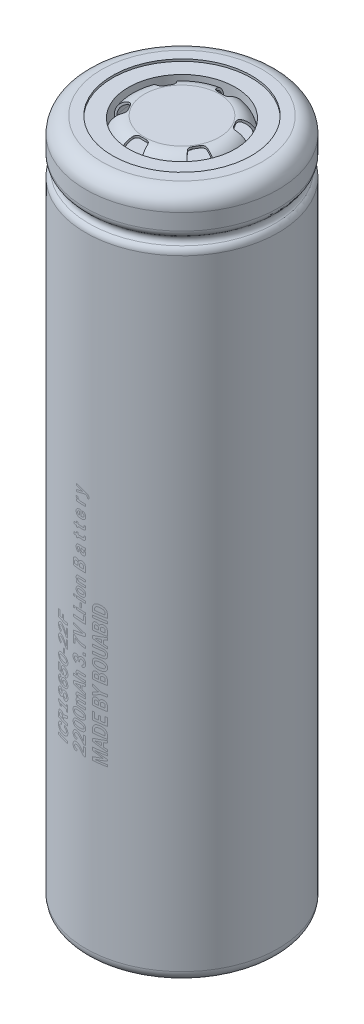
SolidWorks part; units mm, degrees
ref_plane "Plan de face" through (0, 0, 0) normal (0, 0, 1) x (1, 0, 0)
ref_plane "Plan de dessus" through (0, 0, 0) normal (0, 1, 0) x (1, 0, 0)
ref_plane "Plan de droite" through (0, 0, 0) normal (1, 0, 0) x (0, 0, -1)
sketch "Sketch1" plane through (0, 0, 0) normal (0, 0, 1) x (1, 0, 0)
  line L0 (0, 0) -> (0, 62)
  line L1 (5, 64) -> (7.5, 64)
  line L2 (9, 62.5) -> (9, 61)
  line L3 (8, 0) -> (0, 0)
  line L4 (9, 59) -> (9, 1)
  line L5 (1.25, 62) -> (4.8, 62)
  line L6 (5, 64) -> (5, 62) construction
  line L7 (0, 63.8) -> (3.5, 63.8) construction
  line L8 (0, 64) -> (3.5, 64)
  line L9 (5, 62.5) -> (5, 64)
  line L10 (0, 64) -> (0, 62)
  line L11 (1.25, 63.8) -> (1.25, 62)
  line L12 (1.25, 63.8) -> (3.5, 63.8)
  line L13 (4.8, 62) -> (4.8, 62.5)
  line L14 (5, 62) -> (5, 62.5) construction
  line L15 (5, 62) -> (4.8, 62) construction
  arc A0 (9, 1) -> (8, 0) centre (8, 1) cw
  arc A1 (7.5, 64) -> (9, 62.5) centre (7.5, 62.5) cw
  arc A2 (8.7, 60.4) -> (8.7, 59.6) centre (9, 60) ccw
  arc A3 (8.7, 60.4) -> (9, 61) centre (8.25, 61) ccw
  arc A4 (8.7, 59.6) -> (9, 59) centre (8.25, 59) cw
  arc A5 (5, 62.5) -> (3.5, 64) centre (3.5, 62.5) ccw
  arc A6 (4.8, 62.5) -> (3.5, 63.8) centre (3.5, 62.5) ccw
  point P7 (9, 0)
  point P10 (9, 64)
  point P18 (9, 59.5)
  dimension "D3" = 1
  dimension "D4" = 1.5
  dimension "D6" = 0.5
  dimension "D7" = 0.75
  dimension "D10" = 1.5
  dimension "D1" = 64
  dimension "D2" = 9
  dimension "D5" = 4
  dimension "D12" = 1.25
  dimension "D11" = 0.2
revolve "Revolve1" add sketch "Sketch1" angle 360 about L0 region at (4.5078, 31.6082, 0)
sketch "Sketch2" plane through (0, 64, 0) normal (0, 1, 0) x (1, 0, 0)
  circle A0 centre (0, 0) radius 6.5
  circle A1 centre (0, 0) radius 5
  dimension "D1" = 13
extrude "Cut-Extrude1" cut sketch "Sketch2" against normal blind 0.2
sketch "Sketch3" plane through (0, 0, 0) normal (0, -1, 0) x (1, 0, 0)
  circle A0 centre (0, 0) radius 6.5
  dimension "D1" = 13
extrude "Cut-Extrude2" cut sketch "Sketch3" against normal blind 0.2
sketch "Sketch4" plane through (0, 64, 0) normal (0, 1, 0) x (1, 0, 0)
  line L0 (0.9892, 4.9012) -> (0.6775, 3.8948)
  line L1 (0.2954, 3.6132) -> (-0.2954, 3.6132)
  line L2 (-0.6775, 3.8948) -> (-0.9892, 4.9012)
  line L3 (0.9892, 4.9012) -> (-0.9892, 4.9012) construction
  line L4 (4.7391, 1.5939) -> (3.7118, 1.3607)
  line L5 (3.2768, 1.5508) -> (2.9814, 2.0624)
  line L6 (3.0343, 2.5341) -> (3.7499, 3.3073)
  line L7 (3.7499, -3.3073) -> (3.0343, -2.5341)
  line L8 (2.9814, -2.0624) -> (3.2768, -1.5508)
  line L9 (3.7118, -1.3607) -> (4.7391, -1.5939)
  line L10 (-0.9892, -4.9012) -> (-0.6775, -3.8948)
  line L11 (-0.2954, -3.6132) -> (0.2954, -3.6132)
  line L12 (0.6775, -3.8948) -> (0.9892, -4.9012)
  line L13 (-4.7391, -1.5939) -> (-3.7118, -1.3607)
  line L14 (-3.2768, -1.5508) -> (-2.9814, -2.0624)
  line L15 (-3.0343, -2.5341) -> (-3.7499, -3.3073)
  line L16 (-3.7499, 3.3073) -> (-3.0343, 2.5341)
  line L17 (-2.9814, 2.0624) -> (-3.2768, 1.5508)
  line L18 (-3.7118, 1.3607) -> (-4.7391, 1.5939)
  arc A0 (-4.7391, -1.5939) -> (-3.7499, -3.3073) centre (0, 0) ccw
  circle A1 centre (0, 0) radius 5 construction
  arc A2 (-0.2954, 3.6132) -> (-0.6775, 3.8948) centre (-0.2954, 4.0132) cw
  arc A3 (0.6775, 3.8948) -> (0.2954, 3.6132) centre (0.2954, 4.0132) cw
  arc A4 (3.7118, 1.3607) -> (3.2768, 1.5508) centre (3.6232, 1.7508) cw
  arc A5 (2.9814, 2.0624) -> (3.0343, 2.5341) centre (3.3278, 2.2624) cw
  arc A6 (3.0343, -2.5341) -> (2.9814, -2.0624) centre (3.3278, -2.2624) cw
  arc A7 (3.2768, -1.5508) -> (3.7118, -1.3607) centre (3.6232, -1.7508) cw
  arc A8 (-0.6775, -3.8948) -> (-0.2954, -3.6132) centre (-0.2954, -4.0132) cw
  arc A9 (0.2954, -3.6132) -> (0.6775, -3.8948) centre (0.2954, -4.0132) cw
  arc A10 (-3.7118, -1.3607) -> (-3.2768, -1.5508) centre (-3.6232, -1.7508) cw
  arc A11 (-2.9814, -2.0624) -> (-3.0343, -2.5341) centre (-3.3278, -2.2624) cw
  arc A12 (-3.0343, 2.5341) -> (-2.9814, 2.0624) centre (-3.3278, 2.2624) cw
  arc A13 (-3.2768, 1.5508) -> (-3.7118, 1.3607) centre (-3.6232, 1.7508) cw
  arc A14 (-0.9892, -4.9012) -> (0.9892, -4.9012) centre (0, 0) ccw
  arc A15 (3.7499, -3.3073) -> (4.7391, -1.5939) centre (0, 0) ccw
  arc A16 (4.7391, 1.5939) -> (3.7499, 3.3073) centre (0, 0) ccw
  arc A17 (0.9892, 4.9012) -> (-0.9892, 4.9012) centre (0, 0) ccw
  arc A18 (-3.7499, 3.3073) -> (-4.7391, 1.5939) centre (0, 0) ccw
  point P5 (0, 3.6132)
  point P18 (0.5903, 3.6132)
  point P57 (0, 0)
  dimension "D1" = 0.4
  dimension "D2" = 6
extrude "Cut-Extrude3" cut sketch "Sketch4" against normal up to surface (2 mm away) up to face at (0, 62, -4.8)
sketch "Sketch5" plane through (0, 0, 0) normal (0, 0, 1) x (1, 0, 0)
  line L0 (-3.1397, 16.5528) -> (-3.1397, 16.7587)
  line L1 (-0.0296, 16.4327) -> (-0.0296, 38.8264) construction
  line L2 (1.8454, 16.4327) -> (1.8454, 44.3002) construction
  line L3 (1.8454, 16.4327) -> (-0.0296, 16.4327) construction
  line L4 (-0.0296, 16.4327) -> (-1.9046, 16.4327) construction
  line L5 (-3.1397, 16.7587) -> (-1.9046, 16.7587)
  line L6 (-1.9046, 16.7587) -> (-1.9046, 16.5528)
  line L7 (-1.9046, 16.5528) -> (-3.1397, 16.5528)
  line L8 (-2.3335, 17.6163) -> (-2.3066, 17.805)
  line L9 (-2.7387, 17.805) -> (-2.7108, 17.6163)
  line L10 (-3.1397, 17.9766) -> (-3.1397, 18.3515)
  line L11 (-2.4618, 18.5657) -> (-1.9046, 18.7999)
  line L12 (-1.9046, 18.7999) -> (-1.9046, 18.5767)
  line L13 (-1.9046, 18.5767) -> (-2.4192, 18.3848)
  line L14 (-2.4192, 18.3848) -> (-2.4192, 18.1824)
  line L15 (-2.4192, 18.1824) -> (-1.9046, 18.1824)
  line L16 (-1.9046, 18.1824) -> (-1.9046, 17.9766)
  line L17 (-1.9046, 17.9766) -> (-3.1397, 17.9766)
  line L18 (-2.9853, 18.1824) -> (-2.5736, 18.1824)
  line L19 (-2.5736, 18.1824) -> (-2.5736, 18.3389)
  line L20 (-2.9853, 18.3408) -> (-2.9853, 18.1824)
  line L21 (-3.1397, 19.3146) -> (-3.1397, 19.4689)
  line L22 (-3.1397, 19.4689) -> (-2.059, 19.4689)
  line L23 (-2.059, 19.4689) -> (-2.059, 19.6748)
  line L24 (-2.059, 19.6748) -> (-1.9046, 19.6748)
  line L25 (-1.9046, 19.6748) -> (-1.9046, 19.0573)
  line L26 (-1.9046, 19.0573) -> (-2.059, 19.0573)
  line L27 (-2.059, 19.0573) -> (-2.059, 19.2631)
  line L28 (-2.059, 19.2631) -> (-2.8869, 19.2631)
  line L29 (-2.7108, 19.0573) -> (-2.8995, 19.0573)
  line L30 (-2.851, 21.596) -> (-2.7966, 21.4245)
  line L31 (-3.1397, 21.819) -> (-3.1397, 22.4708)
  line L32 (-3.1397, 22.4708) -> (-2.9681, 22.4518)
  line L33 (-2.9681, 22.4518) -> (-2.9681, 21.946)
  line L34 (-2.9681, 21.946) -> (-2.6122, 21.9297)
  line L35 (-2.2037, 21.7332) -> (-2.2477, 21.9219)
  line L36 (-2.4364, 21.9428) -> (-2.4685, 21.7847)
  line L37 (-2.4685, 21.7847) -> (-3.1397, 21.819)
  line L38 (-2.4364, 23.6201) -> (-2.4364, 24.0147)
  line L39 (-2.4364, 24.0147) -> (-2.282, 24.0147)
  line L40 (-2.282, 24.0147) -> (-2.282, 23.6201)
  line L41 (-2.282, 23.6201) -> (-2.4364, 23.6201)
  line L42 (-2.7451, 24.3406) -> (-2.7835, 24.1519)
  line L43 (-2.0761, 24.3577) -> (-2.0761, 24.9238)
  line L44 (-2.0761, 24.9238) -> (-1.9046, 24.9147)
  line L45 (-1.9046, 24.9147) -> (-1.9046, 24.1519)
  line L46 (-1.9046, 24.1519) -> (-2.0745, 24.1519)
  line L47 (-2.7451, 25.284) -> (-2.7835, 25.0954)
  line L48 (-2.0761, 25.3012) -> (-2.0761, 25.8673)
  line L49 (-2.0761, 25.8673) -> (-1.9046, 25.8582)
  line L50 (-1.9046, 25.8582) -> (-1.9046, 25.0954)
  line L51 (-1.9046, 25.0954) -> (-2.0745, 25.0954)
  line L52 (-3.1397, 26.0903) -> (-3.1397, 26.7764)
  line L53 (-3.1397, 26.7764) -> (-2.9681, 26.7764)
  line L54 (-2.9681, 26.7764) -> (-2.9681, 26.2961)
  line L55 (-2.9681, 26.2961) -> (-2.6079, 26.2961)
  line L56 (-2.6079, 26.2961) -> (-2.6079, 26.6735)
  line L57 (-2.6079, 26.6735) -> (-2.4364, 26.6735)
  line L58 (-2.4364, 26.6735) -> (-2.4364, 26.2961)
  line L59 (-2.4364, 26.2961) -> (-1.9046, 26.2961)
  line L60 (-1.9046, 26.2961) -> (-1.9046, 26.0903)
  line L61 (-1.9046, 26.0903) -> (-3.1397, 26.0903)
  line L62 (-0.8701, 16.69) -> (-0.9085, 16.5013)
  line L63 (-0.2011, 16.7072) -> (-0.2011, 17.2733)
  line L64 (-0.2011, 17.2733) -> (-0.0296, 17.2642)
  line L65 (-0.0296, 17.2642) -> (-0.0296, 16.5013)
  line L66 (-0.0296, 16.5013) -> (-0.1995, 16.5013)
  line L67 (-0.8701, 17.6335) -> (-0.9085, 17.4448)
  line L68 (-0.2011, 17.6506) -> (-0.2011, 18.2167)
  line L69 (-0.2011, 18.2167) -> (-0.0296, 18.2076)
  line L70 (-0.0296, 18.2076) -> (-0.0296, 17.4448)
  line L71 (-0.0296, 17.4448) -> (-0.1995, 17.4448)
  line L72 (-0.9387, 20.3095) -> (-0.9387, 20.481)
  line L73 (-0.9387, 20.481) -> (-0.7964, 20.481)
  line L74 (-0.6021, 21.3902) -> (-0.0296, 21.3902)
  line L75 (-0.0296, 21.3902) -> (-0.0296, 21.2015)
  line L76 (-0.0296, 21.2015) -> (-0.5833, 21.2015)
  line L77 (-0.5568, 20.9442) -> (-0.0296, 20.9442)
  line L78 (-0.0296, 20.9442) -> (-0.0296, 20.7555)
  line L79 (-0.0296, 20.7555) -> (-0.5772, 20.7555)
  line L80 (-0.5522, 20.4982) -> (-0.0296, 20.4982)
  line L81 (-0.0296, 20.4982) -> (-0.0296, 20.3095)
  line L82 (-0.0296, 20.3095) -> (-0.9387, 20.3095)
  line L83 (-1.2647, 21.8375) -> (-1.2647, 22.0862)
  line L84 (-1.2647, 22.0862) -> (-0.0296, 22.4194)
  line L85 (-0.0296, 22.4194) -> (-0.0296, 22.2122)
  line L86 (-0.0296, 22.2122) -> (-0.3384, 22.1334)
  line L87 (-0.3384, 22.1334) -> (-0.3384, 21.7657)
  line L88 (-0.3384, 21.7657) -> (-0.0296, 21.6882)
  line L89 (-0.0296, 21.6882) -> (-0.0296, 21.4931)
  line L90 (-0.0296, 21.4931) -> (-1.2647, 21.8375)
  line L91 (-0.4927, 22.0937) -> (-1.0655, 21.9477)
  line L92 (-1.0655, 21.9477) -> (-0.4927, 21.8043)
  line L93 (-0.4927, 21.8043) -> (-0.4927, 22.0937)
  line L94 (-1.2647, 22.5051) -> (-1.2647, 22.6938)
  line L95 (-1.2647, 22.6938) -> (-0.8144, 22.6938)
  line L96 (-0.5994, 23.157) -> (-0.0296, 23.157)
  line L97 (-0.0296, 23.157) -> (-0.0296, 22.9683)
  line L98 (-0.0296, 22.9683) -> (-0.5959, 22.9683)
  line L99 (-0.5442, 22.6938) -> (-0.0296, 22.6938)
  line L100 (-0.0296, 22.6938) -> (-0.0296, 22.5051)
  line L101 (-0.0296, 22.5051) -> (-1.2647, 22.5051)
  line L102 (-0.9387, 23.8431) -> (-0.9789, 23.6716)
  line L103 (-0.3325, 23.6373) -> (-0.3727, 23.8088)
  line L104 (-0.5957, 23.9892) -> (-0.5957, 23.9117)
  line L105 (-0.5957, 23.9117) -> (-0.7501, 23.9117)
  line L106 (-0.7501, 23.9117) -> (-0.7501, 23.9865)
  line L107 (-0.2697, 24.6665) -> (-0.2697, 24.8724)
  line L108 (-0.2697, 24.8724) -> (-0.0296, 24.8724)
  line L109 (-0.0296, 24.8724) -> (-0.0296, 24.6665)
  line L110 (-0.0296, 24.6665) -> (-0.2697, 24.6665)
  line L111 (-1.2647, 25.1468) -> (-1.2647, 25.8501)
  line L112 (-1.2647, 25.8501) -> (-1.1207, 25.8501)
  line L113 (-0.0296, 25.507) -> (-0.0296, 25.3012)
  line L114 (-1.0931, 25.6689) -> (-1.0931, 25.1297)
  line L115 (-1.0931, 25.1297) -> (-1.2647, 25.1468)
  line L116 (-1.2647, 25.9359) -> (-1.2647, 26.1508)
  line L117 (-1.2647, 26.1508) -> (-0.2794, 26.3905)
  line L118 (-0.2794, 26.3905) -> (-1.2647, 26.6301)
  line L119 (-1.2647, 26.6301) -> (-1.2647, 26.8107)
  line L120 (-1.2647, 26.8107) -> (-0.0296, 26.4926)
  line L121 (-0.0296, 26.4926) -> (-0.0296, 26.254)
  line L122 (-0.0296, 26.254) -> (-1.2647, 25.9359)
  line L123 (-1.2647, 27.2567) -> (-1.2647, 27.4626)
  line L124 (-1.2647, 27.4626) -> (-0.2011, 27.4626)
  line L125 (-0.2011, 27.4626) -> (-0.2011, 27.8914)
  line L126 (-0.2011, 27.8914) -> (-0.0296, 27.8914)
  line L127 (-0.0296, 27.8914) -> (-0.0296, 27.2567)
  line L128 (-0.0296, 27.2567) -> (-1.2647, 27.2567)
  line L129 (-1.0588, 28.2002) -> (-1.0588, 28.0115)
  line L130 (-1.0588, 28.0115) -> (-1.2647, 28.0115)
  line L131 (-1.2647, 28.0115) -> (-1.2647, 28.2002)
  line L132 (-1.2647, 28.2002) -> (-1.0588, 28.2002)
  line L133 (-0.9387, 28.0115) -> (-0.9387, 28.2002)
  line L134 (-0.9387, 28.2002) -> (-0.0296, 28.2002)
  line L135 (-0.0296, 28.2002) -> (-0.0296, 28.0115)
  line L136 (-0.0296, 28.0115) -> (-0.9387, 28.0115)
  line L137 (-0.5614, 28.3717) -> (-0.5614, 28.7662)
  line L138 (-0.5614, 28.7662) -> (-0.407, 28.7662)
  line L139 (-0.407, 28.7662) -> (-0.407, 28.3717)
  line L140 (-0.407, 28.3717) -> (-0.5614, 28.3717)
  line L141 (-1.0588, 29.1436) -> (-1.0588, 28.9549)
  line L142 (-1.0588, 28.9549) -> (-1.2647, 28.9549)
  line L143 (-1.2647, 28.9549) -> (-1.2647, 29.1436)
  line L144 (-1.2647, 29.1436) -> (-1.0588, 29.1436)
  line L145 (-0.9387, 28.9549) -> (-0.9387, 29.1436)
  line L146 (-0.9387, 29.1436) -> (-0.0296, 29.1436)
  line L147 (-0.0296, 29.1436) -> (-0.0296, 28.9549)
  line L148 (-0.0296, 28.9549) -> (-0.9387, 28.9549)
  line L149 (-0.9387, 30.2072) -> (-0.9387, 30.3787)
  line L150 (-0.9387, 30.3787) -> (-0.7945, 30.3787)
  line L151 (-0.6128, 30.859) -> (-0.0296, 30.859)
  line L152 (-0.0296, 30.859) -> (-0.0296, 30.6703)
  line L153 (-0.0296, 30.6703) -> (-0.5994, 30.6703)
  line L154 (-0.5335, 30.3958) -> (-0.0296, 30.3958)
  line L155 (-0.0296, 30.3958) -> (-0.0296, 30.2072)
  line L156 (-0.0296, 30.2072) -> (-0.9387, 30.2072)
  line L157 (-1.2647, 31.4251) -> (-1.2647, 31.8033)
  line L158 (-0.0296, 31.8067) -> (-0.0296, 31.4251)
  line L159 (-0.0296, 31.4251) -> (-1.2647, 31.4251)
  line L160 (-0.7501, 31.6309) -> (-0.7501, 31.7566)
  line L161 (-1.1103, 31.7762) -> (-1.1103, 31.6309)
  line L162 (-1.1103, 31.6309) -> (-0.7501, 31.6309)
  line L163 (-0.2011, 31.6309) -> (-0.2011, 31.7899)
  line L164 (-0.5957, 31.7732) -> (-0.5957, 31.6309)
  line L165 (-0.5957, 31.6309) -> (-0.2011, 31.6309)
  line L166 (-0.6814, 32.9346) -> (-0.7037, 32.7631)
  line L167 (-0.5876, 33.4149) -> (-0.2797, 33.4149)
  line L168 (-0.0296, 33.431) -> (-0.0296, 33.2525)
  line L169 (-0.5949, 33.2262) -> (-0.6302, 33.2262)
  line L170 (-0.4287, 33.2262) -> (-0.4721, 33.2262)
  line L171 (-1.1797, 33.9914) -> (-1.196, 34.1697)
  line L172 (-1.196, 34.1697) -> (-0.9387, 34.1697)
  line L173 (-0.9387, 34.1697) -> (-0.9387, 34.3412)
  line L174 (-0.9387, 34.3412) -> (-0.7844, 34.3412)
  line L175 (-0.7844, 34.3412) -> (-0.7844, 34.1697)
  line L176 (-0.7844, 34.1697) -> (-0.3853, 34.1697)
  line L177 (-0.1733, 34.3755) -> (-0.0283, 34.3755)
  line L178 (-0.3748, 33.981) -> (-0.7844, 33.981)
  line L179 (-0.7844, 33.981) -> (-0.7844, 33.8609)
  line L180 (-0.7844, 33.8609) -> (-0.9387, 33.8609)
  line L181 (-0.9387, 33.8609) -> (-0.9387, 33.981)
  line L182 (-0.9387, 33.981) -> (-1.1797, 33.9914)
  line L183 (-1.1797, 34.832) -> (-1.196, 35.0102)
  line L184 (-1.196, 35.0102) -> (-0.9387, 35.0102)
  line L185 (-0.9387, 35.0102) -> (-0.9387, 35.1817)
  line L186 (-0.9387, 35.1817) -> (-0.7844, 35.1817)
  line L187 (-0.7844, 35.1817) -> (-0.7844, 35.0102)
  line L188 (-0.7844, 35.0102) -> (-0.3853, 35.0102)
  line L189 (-0.1733, 35.216) -> (-0.0283, 35.216)
  line L190 (-0.3748, 34.8215) -> (-0.7844, 34.8215)
  line L191 (-0.7844, 34.8215) -> (-0.7844, 34.7014)
  line L192 (-0.7844, 34.7014) -> (-0.9387, 34.7014)
  line L193 (-0.9387, 34.7014) -> (-0.9387, 34.8215)
  line L194 (-0.9387, 34.8215) -> (-1.1797, 34.832)
  line L195 (-0.4584, 36.3139) -> (-0.4584, 35.8119)
  line L196 (-0.3212, 36.1423) -> (-0.299, 36.3139)
  line L197 (-0.5957, 35.8164) -> (-0.5957, 36.1252)
  line L198 (-0.9387, 36.8113) -> (-0.9387, 36.9829)
  line L199 (-0.9387, 36.9829) -> (-0.7388, 36.9829)
  line L200 (-0.9532, 37.2402) -> (-0.7645, 37.2402)
  line L201 (-0.4954, 37) -> (-0.0296, 37)
  line L202 (-0.0296, 37) -> (-0.0296, 36.8113)
  line L203 (-0.0296, 36.8113) -> (-0.9387, 36.8113)
  line L204 (-0.9387, 37.5489) -> (-0.9387, 37.7277)
  line L205 (-0.9387, 37.7277) -> (-0.2783, 37.8979)
  line L206 (-0.2783, 37.8979) -> (-0.9387, 38.0737)
  line L207 (-0.9387, 38.0737) -> (-0.9387, 38.2351)
  line L208 (-0.9387, 38.2351) -> (0.028, 37.9365)
  line L209 (0.2837, 37.5661) -> (0.1355, 37.5661)
  line L210 (-0.0601, 37.81) -> (-0.9387, 37.5489)
  line L211 (0.6104, 16.5528) -> (0.6104, 16.8549)
  line L212 (0.6104, 16.8549) -> (1.5007, 17.098)
  line L213 (1.5007, 17.098) -> (0.6104, 17.3472)
  line L214 (0.6104, 17.3472) -> (0.6104, 17.6335)
  line L215 (0.6104, 17.6335) -> (1.8454, 17.6335)
  line L216 (1.8454, 17.6335) -> (1.8454, 17.4448)
  line L217 (1.8454, 17.4448) -> (0.7913, 17.4448)
  line L218 (0.7913, 17.4448) -> (1.8454, 17.1551)
  line L219 (1.8454, 17.1551) -> (1.8454, 17.0087)
  line L220 (1.8454, 17.0087) -> (0.7905, 16.7243)
  line L221 (0.7905, 16.7243) -> (1.8454, 16.7243)
  line L222 (1.8454, 16.7243) -> (1.8454, 16.5528)
  line L223 (1.8454, 16.5528) -> (0.6104, 16.5528)
  line L224 (0.6104, 18.098) -> (0.6104, 18.3467)
  line L225 (0.6104, 18.3467) -> (1.8454, 18.6799)
  line L226 (1.8454, 18.6799) -> (1.8454, 18.4727)
  line L227 (1.8454, 18.4727) -> (1.5367, 18.3939)
  line L228 (1.5367, 18.3939) -> (1.5367, 18.0262)
  line L229 (1.5367, 18.0262) -> (1.8454, 17.9487)
  line L230 (1.8454, 17.9487) -> (1.8454, 17.7536)
  line L231 (1.8454, 17.7536) -> (0.6104, 18.098)
  line L232 (1.3823, 18.3542) -> (0.8095, 18.2081)
  line L233 (0.8095, 18.2081) -> (1.3823, 18.0647)
  line L234 (1.3823, 18.0647) -> (1.3823, 18.3542)
  line L235 (0.6104, 18.7828) -> (0.6104, 19.0648)
  line L236 (1.8454, 19.0803) -> (1.8454, 18.7828)
  line L237 (1.8454, 18.7828) -> (0.6104, 18.7828)
  line L238 (0.7819, 18.9886) -> (1.6739, 18.9886)
  line L239 (1.6739, 18.9886) -> (1.6739, 19.0747)
  line L240 (0.7819, 19.0747) -> (0.7819, 18.9886)
  line L241 (0.6104, 19.8292) -> (0.6104, 20.5496)
  line L242 (0.6104, 20.5496) -> (0.7819, 20.5496)
  line L243 (0.7819, 20.5496) -> (0.7819, 20.035)
  line L244 (0.7819, 20.035) -> (1.125, 20.035)
  line L245 (1.125, 20.035) -> (1.125, 20.4295)
  line L246 (1.125, 20.4295) -> (1.2965, 20.4295)
  line L247 (1.2965, 20.4295) -> (1.2965, 20.035)
  line L248 (1.2965, 20.035) -> (1.6739, 20.035)
  line L249 (1.6739, 20.035) -> (1.6739, 20.5496)
  line L250 (1.6739, 20.5496) -> (1.8454, 20.5496)
  line L251 (1.8454, 20.5496) -> (1.8454, 19.8292)
  line L252 (1.8454, 19.8292) -> (0.6104, 19.8292)
  line L253 (0.6104, 21.0299) -> (0.6104, 21.4081)
  line L254 (1.8454, 21.4116) -> (1.8454, 21.0299)
  line L255 (1.8454, 21.0299) -> (0.6104, 21.0299)
  line L256 (1.125, 21.2358) -> (1.125, 21.3615)
  line L257 (0.7647, 21.381) -> (0.7647, 21.2358)
  line L258 (0.7647, 21.2358) -> (1.125, 21.2358)
  line L259 (1.6739, 21.2358) -> (1.6739, 21.3947)
  line L260 (1.2793, 21.3781) -> (1.2793, 21.2358)
  line L261 (1.2793, 21.2358) -> (1.6739, 21.2358)
  line L262 (0.6104, 21.8533) -> (0.6104, 22.0817)
  line L263 (0.6104, 22.0817) -> (1.1303, 22.3218)
  line L264 (1.1303, 22.3218) -> (0.6104, 22.555)
  line L265 (0.6104, 22.555) -> (0.6104, 22.7453)
  line L266 (0.6104, 22.7453) -> (1.3233, 22.4022)
  line L267 (1.3233, 22.4022) -> (1.8454, 22.4022)
  line L268 (1.8454, 22.4022) -> (1.8454, 22.1964)
  line L269 (1.8454, 22.1964) -> (1.3233, 22.1964)
  line L270 (1.3233, 22.1964) -> (0.6104, 21.8533)
  line L271 (0.6104, 23.1398) -> (0.6104, 23.518)
  line L272 (1.8454, 23.5215) -> (1.8454, 23.1398)
  line L273 (1.8454, 23.1398) -> (0.6104, 23.1398)
  line L274 (1.125, 23.3457) -> (1.125, 23.4714)
  line L275 (0.7647, 23.4909) -> (0.7647, 23.3457)
  line L276 (0.7647, 23.3457) -> (1.125, 23.3457)
  line L277 (1.6739, 23.3457) -> (1.6739, 23.5046)
  line L278 (1.2793, 23.488) -> (1.2793, 23.3457)
  line L279 (1.2793, 23.3457) -> (1.6739, 23.3457)
  line L280 (0.6104, 25.1983) -> (0.6104, 25.4041)
  line L281 (0.6104, 25.4041) -> (1.3713, 25.4041)
  line L282 (1.3675, 25.7815) -> (0.6104, 25.7815)
  line L283 (0.6104, 25.7815) -> (0.6104, 25.9702)
  line L284 (0.6104, 25.9702) -> (1.3598, 25.9702)
  line L285 (1.3734, 25.1983) -> (0.6104, 25.1983)
  line L286 (0.6104, 26.4347) -> (0.6104, 26.6834)
  line L287 (0.6104, 26.6834) -> (1.8454, 27.0166)
  line L288 (1.8454, 27.0166) -> (1.8454, 26.8094)
  line L289 (1.8454, 26.8094) -> (1.5367, 26.7306)
  line L290 (1.5367, 26.7306) -> (1.5367, 26.3629)
  line L291 (1.5367, 26.3629) -> (1.8454, 26.2854)
  line L292 (1.8454, 26.2854) -> (1.8454, 26.0903)
  line L293 (1.8454, 26.0903) -> (0.6104, 26.4347)
  line L294 (1.3823, 26.6909) -> (0.8095, 26.5448)
  line L295 (0.8095, 26.5448) -> (1.3823, 26.4014)
  line L296 (1.3823, 26.4014) -> (1.3823, 26.6909)
  line L297 (0.6104, 27.1195) -> (0.6104, 27.4977)
  line L298 (1.8454, 27.5012) -> (1.8454, 27.1195)
  line L299 (1.8454, 27.1195) -> (0.6104, 27.1195)
  line L300 (1.125, 27.3253) -> (1.125, 27.451)
  line L301 (0.7647, 27.4706) -> (0.7647, 27.3253)
  line L302 (0.7647, 27.3253) -> (1.125, 27.3253)
  line L303 (1.6739, 27.3253) -> (1.6739, 27.4843)
  line L304 (1.2793, 27.4677) -> (1.2793, 27.3253)
  line L305 (1.2793, 27.3253) -> (1.6739, 27.3253)
  line L306 (0.6104, 28.1316) -> (0.6104, 28.3374)
  line L307 (0.6104, 28.3374) -> (1.8454, 28.3374)
  line L308 (1.8454, 28.3374) -> (1.8454, 28.1316)
  line L309 (1.8454, 28.1316) -> (0.6104, 28.1316)
  line L310 (0.6104, 28.5776) -> (0.6104, 28.8595)
  line L311 (1.8454, 28.8751) -> (1.8454, 28.5776)
  line L312 (1.8454, 28.5776) -> (0.6104, 28.5776)
  line L313 (0.7819, 28.7834) -> (1.6739, 28.7834)
  line L314 (1.6739, 28.7834) -> (1.6739, 28.8694)
  line L315 (0.7819, 28.8694) -> (0.7819, 28.7834)
  spline S0 degree 3 poles (-2.3066, 17.805) (-2.2736, 17.8002) (-2.2255, 17.7919) (-2.1648, 17.7741) (-2.1236, 17.7595) (-2.086, 17.742) (-2.0513, 17.7228) (-2.0201, 17.701) (-1.992, 17.677) (-1.9671, 17.651) (-1.9459, 17.6223) (-1.9278, 17.5916) (-1.913, 17.5587) (-1.9015, 17.5236) (-1.8901, 17.4726) (-1.8876, 17.4326) (-1.8875, 17.4054) knots 0 0 0 0 0.15552 0.227024 0.294286 0.358892 0.420002 0.478874 0.535832 0.591462 0.646472 0.701494 0.75718 0.814156 0.873417 1 1 1 1
  spline S1 degree 3 poles (-1.8875, 17.4054) (-1.8874, 17.3704) (-1.8921, 17.319) (-1.9104, 17.2544) (-1.9293, 17.2108) (-1.9536, 17.1707) (-1.9834, 17.1343) (-2.0185, 17.1013) (-2.059, 17.0726) (-2.1037, 17.0472) (-2.1521, 17.0249) (-2.2042, 17.0062) (-2.2599, 16.991) (-2.3191, 16.9789) (-2.4051, 16.9673) (-2.4718, 16.9644) (-2.5173, 16.9645) knots 0 0 0 0 0.12085 0.177013 0.231187 0.284639 0.338376 0.393391 0.450428 0.509448 0.570614 0.634257 0.700511 0.769805 0.842685 1 1 1 1
  spline S2 degree 3 poles (-2.5173, 16.9645) (-2.5659, 16.9646) (-2.6368, 16.9677) (-2.7278, 16.9796) (-2.7896, 16.9921) (-2.8467, 17.0085) (-2.8996, 17.028) (-2.9481, 17.0512) (-2.9916, 17.0784) (-3.0306, 17.1086) (-3.0643, 17.1426) (-3.093, 17.1796) (-3.1166, 17.2199) (-3.1345, 17.2634) (-3.1522, 17.3269) (-3.1567, 17.3773) (-3.1568, 17.4116) knots 0 0 0 0 0.165247 0.240964 0.311996 0.379317 0.442868 0.503614 0.56162 0.617238 0.671166 0.723799 0.776225 0.829211 0.88347 1 1 1 1
  spline S3 degree 3 poles (-3.1568, 17.4116) (-3.1567, 17.4382) (-3.1542, 17.4774) (-3.1428, 17.5274) (-3.1312, 17.5618) (-3.1168, 17.5943) (-3.0987, 17.6246) (-3.0771, 17.6524) (-3.0525, 17.6785) (-3.0246, 17.702) (-2.9933, 17.7233) (-2.959, 17.7427) (-2.921, 17.7593) (-2.8802, 17.7745) (-2.8195, 17.7916) (-2.7717, 17.8005) (-2.7387, 17.805) knots 0 0 0 0 0.125268 0.183858 0.240575 0.295848 0.350667 0.40578 0.461341 0.518565 0.577168 0.638855 0.703723 0.771764 0.843423 1 1 1 1
  spline S4 degree 3 poles (-2.7108, 17.6163) (-2.7324, 17.614) (-2.7637, 17.6095) (-2.8036, 17.6006) (-2.8305, 17.5933) (-2.8551, 17.5843) (-2.8779, 17.5748) (-2.8982, 17.5637) (-2.9167, 17.552) (-2.9328, 17.5388) (-2.9469, 17.5246) (-2.9588, 17.5092) (-2.9686, 17.4926) (-2.976, 17.4749) (-2.9834, 17.4495) (-2.9853, 17.4294) (-2.9853, 17.4159) knots 0 0 0 0 0.172908 0.251715 0.325686 0.395308 0.460406 0.521918 0.579611 0.634792 0.687681 0.738973 0.789427 0.840496 0.891669 1 1 1 1
  spline S5 degree 3 poles (-2.9853, 17.4159) (-2.9853, 17.3978) (-2.9819, 17.3709) (-2.9691, 17.3378) (-2.9557, 17.3153) (-2.9385, 17.2947) (-2.9177, 17.2759) (-2.8932, 17.2589) (-2.8649, 17.2437) (-2.8329, 17.2304) (-2.797, 17.219) (-2.7577, 17.2091) (-2.7145, 17.2011) (-2.6676, 17.1951) (-2.5977, 17.1888) (-2.5432, 17.1874) (-2.5058, 17.1875) knots 0 0 0 0 0.092193 0.13616 0.180045 0.224992 0.272372 0.322392 0.376789 0.43556 0.499202 0.56822 0.642339 0.722703 0.809104 1 1 1 1
  spline S6 degree 3 poles (-2.5058, 17.1875) (-2.4708, 17.1875) (-2.42, 17.1888) (-2.355, 17.1951) (-2.3113, 17.2011) (-2.2711, 17.2091) (-2.2343, 17.219) (-2.2009, 17.2303) (-2.1711, 17.2438) (-2.1448, 17.2591) (-2.1217, 17.2758) (-2.1025, 17.2949) (-2.0863, 17.3153) (-2.0742, 17.338) (-2.0619, 17.371) (-2.0594, 17.3979) (-2.059, 17.4159) knots 0 0 0 0 0.187566 0.272325 0.35076 0.424087 0.492112 0.555025 0.612946 0.667291 0.718008 0.765802 0.811922 0.85718 0.903131 1 1 1 1
  spline S7 degree 3 poles (-2.059, 17.4159) (-2.0591, 17.4302) (-2.0606, 17.4514) (-2.0686, 17.4778) (-2.0761, 17.4958) (-2.0864, 17.5121) (-2.0984, 17.5273) (-2.113, 17.5407) (-2.13, 17.5525) (-2.1486, 17.5634) (-2.1694, 17.5734) (-2.1919, 17.5827) (-2.2166, 17.5909) (-2.2429, 17.5988) (-2.282, 17.6078) (-2.3124, 17.6136) (-2.3335, 17.6163) knots 0 0 0 0 0.114803 0.167591 0.219641 0.269898 0.321116 0.373585 0.427788 0.485624 0.545889 0.611426 0.679966 0.753514 0.830466 1 1 1 1
  spline S8 degree 3 poles (-3.1397, 18.3515) (-3.1397, 18.3833) (-3.1376, 18.4295) (-3.1274, 18.4884) (-3.1178, 18.5278) (-3.1048, 18.5638) (-3.0891, 18.5966) (-3.0706, 18.6262) (-3.0488, 18.6521) (-3.0246, 18.6751) (-2.9976, 18.6946) (-2.9684, 18.7114) (-2.9366, 18.7252) (-2.9022, 18.7354) (-2.8518, 18.7458) (-2.8123, 18.7484) (-2.7853, 18.7485) knots 0 0 0 0 0.156469 0.226957 0.293616 0.355796 0.415389 0.472119 0.527072 0.58151 0.635955 0.690718 0.747248 0.80609 0.867151 1 1 1 1
  spline S9 degree 3 poles (-2.7853, 18.7485) (-2.7498, 18.7484) (-2.6978, 18.7436) (-2.633, 18.724) (-2.5899, 18.7041) (-2.551, 18.6781) (-2.5046, 18.6345) (-2.4768, 18.5947) (-2.4618, 18.5657) knots 0 0 0 0 0.271528 0.39563 0.515287 0.632799 0.751078 1 1 1 1
  spline S10 degree 3 poles (-2.5736, 18.3389) (-2.5732, 18.3554) (-2.5754, 18.3793) (-2.5814, 18.4096) (-2.5879, 18.4299) (-2.5961, 18.4485) (-2.6065, 18.4653) (-2.6185, 18.4805) (-2.6374, 18.498) (-2.6643, 18.5163) (-2.7155, 18.5375) (-2.7581, 18.5429) (-2.7872, 18.5426) knots 0 0 0 0 0.146438 0.213183 0.275946 0.336235 0.394193 0.451451 0.508398 0.62313 0.739925 1 1 1 1
  spline S11 degree 3 poles (-2.7872, 18.5426) (-2.8027, 18.5428) (-2.8253, 18.541) (-2.8542, 18.5362) (-2.8737, 18.5304) (-2.8916, 18.5233) (-2.9079, 18.5146) (-2.9228, 18.5044) (-2.936, 18.4924) (-2.9479, 18.4791) (-2.9578, 18.4638) (-2.9665, 18.4471) (-2.9733, 18.4288) (-2.9788, 18.409) (-2.9837, 18.3796) (-2.9854, 18.3566) (-2.9853, 18.3408) knots 0 0 0 0 0.143362 0.20883 0.270791 0.330468 0.386646 0.441874 0.49628 0.551304 0.606754 0.664395 0.724539 0.78707 0.854166 1 1 1 1
  spline S12 degree 3 poles (-2.8869, 19.2631) (-2.8522, 19.2365) (-2.7866, 19.173) (-2.7348, 19.0979) (-2.7108, 19.0573) knots 0 0 0 0 0.48071 1 1 1 1
  spline S13 degree 3 poles (-2.8995, 19.0573) (-2.914, 19.0826) (-2.9384, 19.1189) (-2.9746, 19.1647) (-3.0035, 19.1978) (-3.0347, 19.2291) (-3.079, 19.2695) (-3.1147, 19.2974) (-3.1397, 19.3146) knots 0 0 0 0 0.246549 0.36974 0.493412 0.617894 0.74358 1 1 1 1
  spline S14 degree 3 poles (-2.572, 20.4263) (-2.5631, 20.4445) (-2.5488, 20.4706) (-2.5275, 20.5032) (-2.5104, 20.5251) (-2.4931, 20.5456) (-2.4747, 20.5642) (-2.4555, 20.5811) (-2.4354, 20.5961) (-2.4145, 20.6094) (-2.3928, 20.6209) (-2.3703, 20.631) (-2.3468, 20.6386) (-2.3227, 20.6448) (-2.289, 20.651) (-2.263, 20.6526) (-2.2455, 20.6525) knots 0 0 0 0 0.143831 0.211762 0.277547 0.341168 0.402798 0.463662 0.523208 0.581271 0.639612 0.698005 0.756346 0.815442 0.875586 1 1 1 1
  spline S15 degree 3 poles (-2.2455, 20.6525) (-2.221, 20.6529) (-2.1846, 20.6492) (-2.1381, 20.6376) (-2.1051, 20.6259) (-2.0739, 20.6101) (-2.0442, 20.5913) (-2.0162, 20.5688) (-1.9898, 20.5432) (-1.9656, 20.5146) (-1.9446, 20.483) (-1.927, 20.4489) (-1.9123, 20.4121) (-1.9012, 20.3726) (-1.8902, 20.315) (-1.8875, 20.27) (-1.8875, 20.2392) knots 0 0 0 0 0.119763 0.177303 0.233864 0.290424 0.347286 0.405316 0.465456 0.526433 0.587758 0.650177 0.713992 0.780666 0.849947 1 1 1 1
  spline S16 degree 3 poles (-1.8875, 20.2392) (-1.8871, 20.2091) (-1.8901, 20.1651) (-1.8999, 20.1089) (-1.9097, 20.0707) (-1.923, 20.0355) (-1.9387, 20.0029) (-1.9575, 19.9731) (-1.9794, 19.9466) (-2.0032, 19.9229) (-2.0291, 19.9025) (-2.0567, 19.8849) (-2.0863, 19.8709) (-2.1175, 19.86) (-2.1622, 19.8488) (-2.1974, 19.8466) (-2.2211, 19.8463) knots 0 0 0 0 0.154855 0.226255 0.293248 0.357525 0.419391 0.479312 0.538097 0.595617 0.651887 0.70786 0.763361 0.819903 0.877641 1 1 1 1
  spline S17 degree 3 poles (-2.2211, 19.8463) (-2.2379, 19.8462) (-2.2628, 19.8478) (-2.2951, 19.854) (-2.3182, 19.8603) (-2.3407, 19.8679) (-2.3623, 19.8777) (-2.383, 19.8893) (-2.4029, 19.9024) (-2.422, 19.9175) (-2.4402, 19.9344) (-2.4576, 19.953) (-2.4743, 19.9732) (-2.4902, 19.9952) (-2.5105, 20.0277) (-2.5241, 20.0537) (-2.5323, 20.0717) knots 0 0 0 0 0.123047 0.18248 0.240873 0.299163 0.356706 0.414555 0.472771 0.532085 0.59289 0.655069 0.718897 0.78516 0.854133 1 1 1 1
  spline S18 degree 3 poles (-2.5323, 20.0717) (-2.5493, 20.0423) (-2.5768, 20.0006) (-2.6224, 19.9552) (-2.6573, 19.9276) (-2.6951, 19.9066) (-2.7491, 19.8865) (-2.7922, 19.8803) (-2.8213, 19.8806) knots 0 0 0 0 0.280116 0.406933 0.527936 0.645732 0.761096 1 1 1 1
  spline S19 degree 3 poles (-2.8213, 19.8806) (-2.8443, 19.8808) (-2.8785, 19.8834) (-2.9222, 19.894) (-2.953, 19.9048) (-2.9824, 19.9185) (-3.0104, 19.9354) (-3.0367, 19.9557) (-3.0615, 19.9787) (-3.0839, 20.0046) (-3.1037, 20.0332) (-3.12, 20.0645) (-3.1333, 20.0983) (-3.1442, 20.1343) (-3.1544, 20.1875) (-3.1565, 20.2291) (-3.1568, 20.2575) knots 0 0 0 0 0.121771 0.179977 0.236937 0.293675 0.351003 0.409185 0.468561 0.529058 0.589739 0.651531 0.715005 0.780937 0.8501 1 1 1 1
  spline S20 degree 3 poles (-3.1568, 20.2575) (-3.1567, 20.2847) (-3.1547, 20.3246) (-3.1452, 20.3755) (-3.1355, 20.4102) (-3.1235, 20.4426) (-3.1085, 20.4725) (-3.0903, 20.4997) (-3.07, 20.5245) (-3.0471, 20.5463) (-3.0231, 20.5659) (-2.9971, 20.582) (-2.9695, 20.5951) (-2.9405, 20.6058) (-2.8989, 20.6153) (-2.8665, 20.6187) (-2.8446, 20.6182) knots 0 0 0 0 0.151721 0.221612 0.288269 0.352054 0.413931 0.474254 0.533645 0.592427 0.64979 0.706134 0.762453 0.819602 0.87791 1 1 1 1
  spline S21 degree 3 poles (-2.8446, 20.6182) (-2.8161, 20.6185) (-2.7739, 20.6125) (-2.7216, 20.5922) (-2.6857, 20.5709) (-2.6528, 20.5434) (-2.6111, 20.4973) (-2.5863, 20.456) (-2.572, 20.4263) knots 0 0 0 0 0.241266 0.357735 0.474013 0.594129 0.720288 1 1 1 1
  spline S22 degree 3 poles (-2.6366, 20.2725) (-2.6497, 20.2964) (-2.6705, 20.3301) (-2.7041, 20.368) (-2.7294, 20.3908) (-2.7563, 20.408) (-2.7938, 20.4244) (-2.8239, 20.4298) (-2.844, 20.4295) knots 0 0 0 0 0.298781 0.431134 0.553818 0.669974 0.779941 1 1 1 1
  spline S23 degree 3 poles (-2.844, 20.4295) (-2.8674, 20.4297) (-2.9021, 20.4241) (-2.9435, 20.4041) (-2.9702, 20.3835) (-2.9924, 20.3581) (-3.0143, 20.3168) (-3.0195, 20.2812) (-3.0196, 20.2572) knots 0 0 0 0 0.25424 0.374113 0.496678 0.618549 0.738454 1 1 1 1
  spline S24 degree 3 poles (-3.0196, 20.2572) (-3.0199, 20.2341) (-3.0141, 20.2001) (-2.9943, 20.1595) (-2.9738, 20.1338) (-2.9488, 20.1126) (-2.9089, 20.0919) (-2.875, 20.0862) (-2.8521, 20.0865) knots 0 0 0 0 0.257816 0.379415 0.501813 0.623148 0.743873 1 1 1 1
  spline S25 degree 3 poles (-2.8521, 20.0865) (-2.8296, 20.0867) (-2.7955, 20.0917) (-2.7547, 20.1122) (-2.7263, 20.1327) (-2.7004, 20.1594) (-2.6669, 20.2044) (-2.6479, 20.2442) (-2.6366, 20.2725) knots 0 0 0 0 0.222938 0.333033 0.447402 0.567818 0.698935 1 1 1 1
  spline S26 degree 3 poles (-2.457, 20.2132) (-2.4452, 20.186) (-2.4251, 20.1479) (-2.3909, 20.1049) (-2.3647, 20.0791) (-2.3358, 20.0596) (-2.2947, 20.0406) (-2.2611, 20.0346) (-2.2386, 20.035) knots 0 0 0 0 0.29735 0.427785 0.549213 0.663798 0.775029 1 1 1 1
  spline S27 degree 3 poles (-2.2386, 20.035) (-2.2238, 20.0346) (-2.2023, 20.0368) (-2.1747, 20.0429) (-2.1558, 20.0493) (-2.1382, 20.0578) (-2.1218, 20.0678) (-2.1069, 20.0802) (-2.0888, 20.0986) (-2.0699, 20.1255) (-2.0472, 20.1752) (-2.0418, 20.2172) (-2.0418, 20.2454) knots 0 0 0 0 0.135949 0.199383 0.260423 0.319824 0.379105 0.437722 0.497801 0.617278 0.738723 1 1 1 1
  spline S28 degree 3 poles (-2.0418, 20.2454) (-2.0416, 20.272) (-2.0472, 20.3113) (-2.068, 20.3588) (-2.0863, 20.3843) (-2.1028, 20.4027) (-2.1168, 20.4144) (-2.1316, 20.4244) (-2.1475, 20.4326) (-2.1644, 20.4391) (-2.1888, 20.4452) (-2.2079, 20.4468) (-2.2209, 20.4467) knots 0 0 0 0 0.263892 0.388195 0.511747 0.573273 0.633703 0.692509 0.750438 0.810246 0.871568 1 1 1 1
  spline S29 degree 3 poles (-2.2209, 20.4467) (-2.2435, 20.4468) (-2.2778, 20.4412) (-2.3187, 20.4205) (-2.3424, 20.4033) (-2.3602, 20.3858) (-2.3739, 20.3696) (-2.3874, 20.3504) (-2.4015, 20.3287) (-2.4151, 20.3038) (-2.4347, 20.2655) (-2.4481, 20.2348) (-2.457, 20.2132) knots 0 0 0 0 0.191744 0.286976 0.385299 0.438164 0.497627 0.563639 0.636324 0.716783 0.803237 1 1 1 1
  spline S30 degree 3 poles (-2.7966, 21.4245) (-2.8273, 21.4179) (-2.8707, 21.4058) (-2.9215, 21.3802) (-2.9511, 21.3586) (-2.9741, 21.3336) (-2.9966, 21.2955) (-3.0025, 21.2623) (-3.0024, 21.2403) knots 0 0 0 0 0.312605 0.44452 0.563923 0.6746 0.780499 1 1 1 1
  spline S31 degree 3 poles (-3.0024, 21.2403) (-3.0024, 21.2224) (-2.9991, 21.1959) (-2.9862, 21.1632) (-2.9726, 21.1412) (-2.9555, 21.1208) (-2.9345, 21.1024) (-2.9097, 21.0862) (-2.8811, 21.0717) (-2.8488, 21.0588) (-2.8125, 21.0478) (-2.7725, 21.0378) (-2.7284, 21.03) (-2.6804, 21.0233) (-2.6085, 21.0158) (-2.5524, 21.0139) (-2.5138, 21.0128) knots 0 0 0 0 0.090337 0.133005 0.176275 0.220405 0.266687 0.31642 0.369616 0.427845 0.491543 0.560712 0.635826 0.717254 0.805122 1 1 1 1
  spline S32 degree 3 poles (-2.5138, 21.0128) (-2.5417, 21.0253) (-2.5806, 21.0475) (-2.624, 21.0862) (-2.6493, 21.1179) (-2.6697, 21.1526) (-2.6884, 21.2048) (-2.6941, 21.2468) (-2.6937, 21.2754) knots 0 0 0 0 0.270519 0.393074 0.511703 0.628567 0.747354 1 1 1 1
  spline S33 degree 3 poles (-2.6937, 21.2754) (-2.6939, 21.2982) (-2.6904, 21.3319) (-2.6793, 21.3753) (-2.6674, 21.406) (-2.6522, 21.4355) (-2.6337, 21.4636) (-2.6118, 21.4903) (-2.5867, 21.5154) (-2.5587, 21.5383) (-2.5283, 21.5586) (-2.4954, 21.5755) (-2.4603, 21.5892) (-2.4228, 21.5999) (-2.3685, 21.6105) (-2.3261, 21.6129) (-2.2973, 21.6132) knots 0 0 0 0 0.11702 0.173544 0.229712 0.286039 0.34379 0.402586 0.46369 0.526075 0.588415 0.651527 0.715715 0.782199 0.851521 1 1 1 1
  spline S34 degree 3 poles (-2.2973, 21.6132) (-2.2678, 21.613) (-2.2244, 21.6106) (-2.1689, 21.599) (-2.1303, 21.5879) (-2.0941, 21.5731) (-2.06, 21.5552) (-2.0286, 21.5334) (-1.9994, 21.5092) (-1.9731, 21.4822) (-1.9502, 21.4528) (-1.9308, 21.4212) (-1.9149, 21.3875) (-1.9026, 21.3517) (-1.8904, 21.3003) (-1.8879, 21.2599) (-1.8875, 21.2326) knots 0 0 0 0 0.140415 0.205982 0.269377 0.331382 0.392082 0.452369 0.512766 0.572626 0.631419 0.689854 0.748647 0.808507 0.869688 1 1 1 1
  spline S35 degree 3 poles (-1.8875, 21.2326) (-1.8877, 21.2035) (-1.8916, 21.1604) (-1.9072, 21.1057) (-1.9235, 21.0675) (-1.9442, 21.0313) (-1.9699, 20.9975) (-2, 20.9659) (-2.0346, 20.9363) (-2.0743, 20.9096) (-2.1191, 20.8867) (-2.169, 20.867) (-2.2242, 20.8515) (-2.2844, 20.8389) (-2.3747, 20.8269) (-2.4454, 20.8244) (-2.494, 20.8241) knots 0 0 0 0 0.105835 0.156614 0.20648 0.256774 0.308126 0.360609 0.415778 0.473452 0.534292 0.599012 0.668432 0.742914 0.822718 1 1 1 1
  spline S36 degree 3 poles (-2.494, 20.8241) (-2.5445, 20.8245) (-2.6182, 20.8269) (-2.7129, 20.839) (-2.777, 20.8512) (-2.8365, 20.8668) (-2.891, 20.8865) (-2.9411, 20.9092) (-2.9861, 20.9357) (-3.0263, 20.9652) (-3.0611, 20.9976) (-3.0909, 21.0321) (-3.115, 21.0696) (-3.134, 21.1095) (-3.1517, 21.1671) (-3.157, 21.2127) (-3.1568, 21.2435) knots 0 0 0 0 0.172556 0.251284 0.325519 0.395287 0.461085 0.523183 0.582659 0.639148 0.692886 0.744595 0.79468 0.844616 0.89478 1 1 1 1
  spline S37 degree 3 poles (-3.1568, 21.2435) (-3.157, 21.2642) (-3.1546, 21.2947) (-3.1471, 21.3344) (-3.139, 21.3626) (-3.1288, 21.3899) (-3.1162, 21.416) (-3.1013, 21.4412) (-3.0842, 21.4653) (-3.0647, 21.4882) (-3.0422, 21.5093) (-3.0169, 21.5282) (-2.989, 21.5455) (-2.9585, 21.561) (-2.9128, 21.5797) (-2.8762, 21.59) (-2.851, 21.596) knots 0 0 0 0 0.121285 0.179615 0.236997 0.293701 0.350813 0.407588 0.465618 0.524494 0.584345 0.646245 0.709966 0.777177 0.847631 1 1 1 1
  spline S38 degree 3 poles (-2.2927, 21.4073) (-2.3119, 21.4071) (-2.34, 21.4061) (-2.3759, 21.401) (-2.4001, 21.3957) (-2.4223, 21.3888) (-2.4427, 21.3804) (-2.4612, 21.3706) (-2.4777, 21.3592) (-2.4922, 21.3466) (-2.5049, 21.3329) (-2.5154, 21.318) (-2.5241, 21.3022) (-2.5311, 21.2855) (-2.5377, 21.2612) (-2.539, 21.2422) (-2.5393, 21.2293) knots 0 0 0 0 0.168104 0.244609 0.316578 0.384474 0.447824 0.508942 0.566755 0.622639 0.676778 0.72941 0.78112 0.834322 0.887725 1 1 1 1
  spline S39 degree 3 poles (-2.5393, 21.2293) (-2.5397, 21.214) (-2.5369, 21.1917) (-2.53, 21.1631) (-2.5216, 21.1438) (-2.5119, 21.1256) (-2.4993, 21.1092) (-2.4848, 21.094) (-2.4623, 21.0762) (-2.4305, 21.0572) (-2.3717, 21.0356) (-2.3238, 21.0298) (-2.2911, 21.0299) knots 0 0 0 0 0.127986 0.187489 0.24583 0.303076 0.36022 0.418406 0.47798 0.600738 0.726185 1 1 1 1
  spline S40 degree 3 poles (-2.2911, 21.0299) (-2.2737, 21.03) (-2.2481, 21.0312) (-2.2152, 21.037) (-2.1923, 21.0431) (-2.1705, 21.0502) (-2.1498, 21.0592) (-2.1305, 21.0704) (-2.1122, 21.0826) (-2.0957, 21.0964) (-2.0813, 21.1116) (-2.0692, 21.1277) (-2.0591, 21.1451) (-2.0514, 21.1636) (-2.0436, 21.1904) (-2.0419, 21.2116) (-2.0418, 21.2259) knots 0 0 0 0 0.146663 0.215602 0.281818 0.34621 0.409689 0.472176 0.534091 0.595117 0.653266 0.709828 0.76558 0.822027 0.879314 1 1 1 1
  spline S41 degree 3 poles (-2.0418, 21.2259) (-2.042, 21.2401) (-2.0436, 21.261) (-2.0503, 21.2874) (-2.0569, 21.3053) (-2.0659, 21.3218) (-2.0769, 21.3367) (-2.0897, 21.3504) (-2.1045, 21.3625) (-2.1214, 21.3729) (-2.14, 21.3823) (-2.1607, 21.3901) (-2.1833, 21.3966) (-2.208, 21.4012) (-2.2446, 21.406) (-2.2731, 21.4072) (-2.2927, 21.4073) knots 0 0 0 0 0.121554 0.177242 0.2309 0.283629 0.336396 0.388568 0.442597 0.498285 0.557786 0.619632 0.686051 0.757324 0.833238 1 1 1 1
  spline S42 degree 3 poles (-2.6122, 21.9297) (-2.6328, 21.9487) (-2.6622, 21.978) (-2.6933, 22.0219) (-2.7125, 22.0545) (-2.7268, 22.0881) (-2.7411, 22.1338) (-2.745, 22.1695) (-2.7451, 22.1932) knots 0 0 0 0 0.277456 0.406267 0.529396 0.649334 0.766354 1 1 1 1
  spline S43 degree 3 poles (-2.7451, 22.1932) (-2.7457, 22.2182) (-2.7415, 22.2549) (-2.7307, 22.3022) (-2.7184, 22.3347) (-2.7031, 22.3655) (-2.6839, 22.394) (-2.6618, 22.421) (-2.636, 22.4454) (-2.6074, 22.4679) (-2.5755, 22.4867) (-2.5412, 22.5033) (-2.5042, 22.5166) (-2.4644, 22.5267) (-2.4064, 22.5371) (-2.3609, 22.5391) (-2.33, 22.5395) knots 0 0 0 0 0.122749 0.180994 0.23767 0.293233 0.349609 0.406044 0.464419 0.523869 0.584328 0.646181 0.71062 0.777276 0.847722 1 1 1 1
  spline S44 degree 3 poles (-2.33, 22.5395) (-2.2969, 22.5389) (-2.2482, 22.5369) (-2.1862, 22.524) (-2.1437, 22.5121) (-2.1044, 22.4956) (-2.0675, 22.4765) (-2.034, 22.4529) (-2.0033, 22.4264) (-1.976, 22.3969) (-1.9523, 22.3649) (-1.9324, 22.3305) (-1.9155, 22.294) (-1.9031, 22.2549) (-1.8906, 22.1989) (-1.8876, 22.155) (-1.8875, 22.1254) knots 0 0 0 0 0.145079 0.212084 0.276412 0.338117 0.398272 0.457806 0.516829 0.575471 0.633327 0.690786 0.749214 0.808799 0.870068 1 1 1 1
  spline S45 degree 3 poles (-1.8875, 22.1254) (-1.8875, 22.1014) (-1.89, 22.066) (-1.8981, 22.0199) (-1.9071, 21.9873) (-1.9184, 21.9558) (-1.9319, 21.9255) (-1.9486, 21.8967) (-1.9672, 21.8691) (-1.9882, 21.8433) (-2.0121, 21.8202) (-2.038, 21.7992) (-2.0665, 21.7808) (-2.0973, 21.765) (-2.1427, 21.7472) (-2.1788, 21.7376) (-2.2037, 21.7332) knots 0 0 0 0 0.12999 0.19263 0.2535 0.313832 0.374001 0.433778 0.494219 0.554558 0.614276 0.674686 0.735399 0.798129 0.862387 1 1 1 1
  spline S46 degree 3 poles (-2.2477, 21.9219) (-2.2193, 21.9285) (-2.1788, 21.9413) (-2.1326, 21.9698) (-2.1057, 21.9945) (-2.0844, 22.023) (-2.0639, 22.0678) (-2.059, 22.1055) (-2.059, 22.131) knots 0 0 0 0 0.284054 0.408164 0.524962 0.637359 0.751227 1 1 1 1
  spline S47 degree 3 poles (-2.059, 22.131) (-2.0593, 22.1468) (-2.0604, 22.1703) (-2.068, 22.1996) (-2.0747, 22.2198) (-2.0844, 22.238) (-2.0956, 22.2549) (-2.1092, 22.2699) (-2.1246, 22.2836) (-2.1425, 22.2951) (-2.162, 22.3058) (-2.1838, 22.3142) (-2.2073, 22.3216) (-2.2333, 22.3267) (-2.2716, 22.3323) (-2.3016, 22.3336) (-2.3222, 22.3336) knots 0 0 0 0 0.125669 0.183955 0.239394 0.293451 0.346382 0.399445 0.453037 0.509104 0.567603 0.628505 0.693566 0.762878 0.837148 1 1 1 1
  spline S48 degree 3 poles (-2.3222, 22.3336) (-2.341, 22.3337) (-2.3684, 22.332) (-2.4037, 22.3271) (-2.4277, 22.3214) (-2.4502, 22.3146) (-2.4708, 22.3056) (-2.49, 22.2955) (-2.5074, 22.2836) (-2.5232, 22.2705) (-2.5367, 22.2556) (-2.5482, 22.2393) (-2.5575, 22.2215) (-2.5645, 22.2022) (-2.5722, 22.174) (-2.5733, 22.1515) (-2.5736, 22.1363) knots 0 0 0 0 0.15551 0.226472 0.294767 0.359042 0.420949 0.480459 0.538464 0.594573 0.649502 0.704654 0.758863 0.815688 0.873763 1 1 1 1
  spline S49 degree 3 poles (-2.5736, 22.1363) (-2.5737, 22.115) (-2.5699, 22.0836) (-2.5551, 22.0449) (-2.5399, 22.0191) (-2.5203, 21.9958) (-2.4872, 21.9676) (-2.4575, 21.9517) (-2.4364, 21.9428) knots 0 0 0 0 0.252433 0.370231 0.486813 0.605387 0.728311 1 1 1 1
  spline S50 degree 3 poles (-2.5369, 23.4829) (-2.4837, 23.4828) (-2.4067, 23.4803) (-2.3083, 23.4693) (-2.2431, 23.4583) (-2.1839, 23.4439) (-2.1305, 23.4263) (-2.083, 23.4055) (-2.0413, 23.3813) (-2.0049, 23.3539) (-1.9734, 23.3236) (-1.9468, 23.2902) (-1.9247, 23.2541) (-1.9082, 23.2145) (-1.8917, 23.1568) (-1.8874, 23.1109) (-1.8875, 23.0798) knots 0 0 0 0 0.184478 0.266771 0.34315 0.413312 0.477954 0.537579 0.592825 0.644796 0.695176 0.743885 0.792381 0.841509 0.892094 1 1 1 1
  spline S51 degree 3 poles (-1.8875, 23.0798) (-1.8874, 23.0481) (-1.8918, 23.0016) (-1.908, 22.9429) (-1.9254, 22.9033) (-1.9472, 22.8666) (-1.9741, 22.8333) (-2.006, 22.8033) (-2.0426, 22.7762) (-2.0841, 22.7527) (-2.1305, 22.7325) (-2.1815, 22.7149) (-2.2373, 22.7009) (-2.2981, 22.69) (-2.3885, 22.6796) (-2.4589, 22.6766) (-2.5074, 22.6767) knots 0 0 0 0 0.113431 0.166327 0.217649 0.268045 0.318588 0.370666 0.424445 0.481222 0.541415 0.605394 0.674103 0.747628 0.826284 1 1 1 1
  spline S52 degree 3 poles (-2.5074, 22.6767) (-2.5608, 22.6767) (-2.6381, 22.6793) (-2.7367, 22.6902) (-2.8018, 22.7014) (-2.8612, 22.7156) (-2.9145, 22.7336) (-2.9621, 22.7543) (-3.0038, 22.7786) (-3.0401, 22.8061) (-3.0711, 22.8367) (-3.0979, 22.8698) (-3.1193, 22.9064) (-3.1365, 22.9455) (-3.1523, 23.0032) (-3.157, 23.0487) (-3.1568, 23.0798) knots 0 0 0 0 0.185094 0.267694 0.343766 0.414227 0.478967 0.538591 0.593836 0.645994 0.695928 0.744637 0.793239 0.842204 0.892405 1 1 1 1
  spline S53 degree 3 poles (-3.1568, 23.0798) (-3.1568, 23.1115) (-3.1527, 23.1581) (-3.1362, 23.2168) (-3.1189, 23.2563) (-3.097, 23.2929) (-3.0703, 23.3266) (-3.0382, 23.3563) (-3.0018, 23.3834) (-2.9601, 23.4068) (-2.9139, 23.4275) (-2.8628, 23.4445) (-2.807, 23.4587) (-2.7462, 23.4695) (-2.6559, 23.4807) (-2.5853, 23.4826) (-2.5369, 23.4829) knots 0 0 0 0 0.113738 0.166322 0.217639 0.268031 0.318819 0.370673 0.424448 0.48122 0.541539 0.605409 0.674113 0.747632 0.826319 1 1 1 1
  spline S54 degree 3 poles (-2.5221, 23.2771) (-2.5633, 23.2771) (-2.6226, 23.2756) (-2.6982, 23.2706) (-2.7475, 23.2654) (-2.7917, 23.2581) (-2.831, 23.2497) (-2.8655, 23.24) (-2.895, 23.2281) (-2.9204, 23.2149) (-2.9422, 23.2) (-2.9611, 23.1841) (-2.976, 23.166) (-2.988, 23.1467) (-2.9993, 23.1183) (-3.0026, 23.0953) (-3.0024, 23.0798) knots 0 0 0 0 0.215883 0.310663 0.396833 0.475095 0.545515 0.607433 0.662455 0.71166 0.757489 0.800291 0.840505 0.880002 0.918857 1 1 1 1
  spline S55 degree 3 poles (-3.0024, 23.0798) (-3.0027, 23.0644) (-2.9992, 23.0417) (-2.9882, 23.0134) (-2.9766, 22.994) (-2.9613, 22.9763) (-2.9431, 22.9599) (-2.9214, 22.9453) (-2.8964, 22.9317) (-2.867, 22.9199) (-2.8328, 22.9099) (-2.7935, 22.9014) (-2.7491, 22.8946) (-2.6997, 22.8889) (-2.6234, 22.8841) (-2.5637, 22.8824) (-2.5221, 22.8825) knots 0 0 0 0 0.080671 0.118909 0.158156 0.198664 0.240755 0.286189 0.335192 0.389768 0.451807 0.521756 0.599927 0.687062 0.78229 1 1 1 1
  spline S56 degree 3 poles (-2.5221, 22.8825) (-2.4778, 22.8824) (-2.4144, 22.8839) (-2.334, 22.8898) (-2.2827, 22.8955) (-2.2375, 22.9031) (-2.1983, 22.9123) (-2.1651, 22.9234) (-2.1377, 22.9364) (-2.115, 22.951) (-2.0955, 22.9663) (-2.0791, 22.9827) (-2.0653, 23) (-2.0549, 23.0186) (-2.0445, 23.0447) (-2.0421, 23.0658) (-2.0418, 23.0798) knots 0 0 0 0 0.232443 0.332497 0.422557 0.502877 0.572748 0.63363 0.685589 0.731718 0.774734 0.815143 0.853186 0.890312 0.926499 1 1 1 1
  spline S57 degree 3 poles (-2.0418, 23.0798) (-2.0417, 23.0955) (-2.0448, 23.119) (-2.0566, 23.1476) (-2.0686, 23.1671) (-2.0838, 23.1852) (-2.1029, 23.2011) (-2.1249, 23.216) (-2.1507, 23.2289) (-2.1804, 23.2405) (-2.215, 23.2501) (-2.2542, 23.2588) (-2.2984, 23.2652) (-2.3474, 23.2705) (-2.4224, 23.2762) (-2.4813, 23.2767) (-2.5221, 23.2771) knots 0 0 0 0 0.082487 0.121929 0.161404 0.201897 0.245028 0.29122 0.340597 0.395849 0.458182 0.528106 0.606178 0.691834 0.786128 1 1 1 1
  spline S58 degree 3 poles (-2.7835, 24.1519) (-2.8124, 24.1574) (-2.8547, 24.1669) (-2.9081, 24.1855) (-2.9443, 24.2017) (-2.978, 24.2195) (-3.0087, 24.24) (-3.0367, 24.2626) (-3.0621, 24.2873) (-3.0842, 24.3141) (-3.1038, 24.3427) (-3.1201, 24.3731) (-3.1336, 24.4052) (-3.144, 24.4392) (-3.1543, 24.4877) (-3.1565, 24.5255) (-3.1568, 24.551) knots 0 0 0 0 0.147089 0.21555 0.28135 0.344518 0.405543 0.465087 0.52367 0.581553 0.638627 0.695822 0.753313 0.812061 0.872597 1 1 1 1
  spline S59 degree 3 poles (-3.1568, 24.551) (-3.1568, 24.5786) (-3.154, 24.6192) (-3.1431, 24.671) (-3.1318, 24.7065) (-3.1177, 24.7399) (-3.0997, 24.7705) (-3.0791, 24.7992) (-3.0549, 24.825) (-3.0285, 24.8482) (-3.0001, 24.8687) (-2.9696, 24.8854) (-2.9378, 24.8999) (-2.9039, 24.9105) (-2.8556, 24.9212) (-2.8178, 24.9236) (-2.7923, 24.9238) knots 0 0 0 0 0.140932 0.20664 0.26978 0.330828 0.390871 0.450589 0.510903 0.570976 0.629792 0.688763 0.748141 0.807963 0.869565 1 1 1 1
  spline S60 degree 3 poles (-2.7923, 24.9238) (-2.7617, 24.9234) (-2.7155, 24.9195) (-2.6557, 24.9037) (-2.6112, 24.888) (-2.5674, 24.8671) (-2.5243, 24.8418) (-2.4816, 24.8121) (-2.4397, 24.7774) (-2.3971, 24.7389) (-2.3542, 24.6962) (-2.3101, 24.6496) (-2.2649, 24.5992) (-2.2191, 24.5445) (-2.1545, 24.4648) (-2.1077, 24.4013) (-2.0761, 24.3577) knots 0 0 0 0 0.09714 0.145968 0.195586 0.24663 0.299419 0.353931 0.411288 0.471629 0.5357 0.603198 0.674988 0.750144 0.829477 1 1 1 1
  spline S61 degree 3 poles (-2.0745, 24.1519) (-2.0994, 24.181) (-2.1359, 24.2237) (-2.1841, 24.2789) (-2.2181, 24.3173) (-2.2509, 24.3534) (-2.2821, 24.3879) (-2.3126, 24.4198) (-2.341, 24.4503) (-2.3688, 24.4781) (-2.395, 24.5041) (-2.4197, 24.5281) (-2.4432, 24.55) (-2.4655, 24.5698) (-2.4863, 24.5877) (-2.5062, 24.6031) (-2.5301, 24.6212) (-2.5591, 24.6405) (-2.5928, 24.6616) (-2.6261, 24.6785) (-2.6583, 24.693) (-2.6898, 24.7039) (-2.7295, 24.7149) (-2.7596, 24.7177) (-2.7792, 24.718) knots 0 0 0 0 0.123915 0.181937 0.237267 0.289907 0.340076 0.387761 0.432782 0.475127 0.515018 0.552049 0.586847 0.619016 0.648576 0.675776 0.700366 0.745781 0.788501 0.82887 0.866821 0.902687 0.93651 1 1 1 1
  spline S62 degree 3 poles (-2.7792, 24.718) (-2.8069, 24.7179) (-2.8477, 24.7132) (-2.8967, 24.6926) (-2.9229, 24.6752) (-2.9411, 24.659) (-2.9529, 24.6454) (-2.9631, 24.6312) (-2.9712, 24.6155) (-2.9777, 24.5991) (-2.9832, 24.5749) (-2.9858, 24.5563) (-2.9853, 24.5435) knots 0 0 0 0 0.274758 0.399442 0.522424 0.583089 0.640673 0.698998 0.755894 0.814619 0.873747 1 1 1 1
  spline S63 degree 3 poles (-2.9853, 24.5435) (-2.9849, 24.53) (-2.9838, 24.5098) (-2.977, 24.4844) (-2.9708, 24.4665) (-2.9619, 24.4501) (-2.9519, 24.4343) (-2.9393, 24.4202) (-2.9252, 24.4068) (-2.9092, 24.3946) (-2.8913, 24.3835) (-2.8714, 24.3737) (-2.8498, 24.3648) (-2.8263, 24.3571) (-2.7914, 24.3479) (-2.764, 24.3432) (-2.7451, 24.3406) knots 0 0 0 0 0.116747 0.172341 0.226358 0.279341 0.332675 0.386654 0.44161 0.499762 0.559525 0.623162 0.689724 0.760992 0.835807 1 1 1 1
  spline S64 degree 3 poles (-2.7835, 25.0954) (-2.8124, 25.1008) (-2.8547, 25.1103) (-2.9081, 25.1289) (-2.9443, 25.1451) (-2.978, 25.1629) (-3.0087, 25.1835) (-3.0367, 25.206) (-3.0621, 25.2307) (-3.0842, 25.2576) (-3.1038, 25.2862) (-3.1201, 25.3166) (-3.1336, 25.3487) (-3.144, 25.3826) (-3.1543, 25.4311) (-3.1565, 25.4689) (-3.1568, 25.4944) knots 0 0 0 0 0.147089 0.21555 0.28135 0.344518 0.405543 0.465087 0.52367 0.581553 0.638627 0.695822 0.753313 0.812061 0.872597 1 1 1 1
  spline S65 degree 3 poles (-3.1568, 25.4944) (-3.1568, 25.5221) (-3.154, 25.5626) (-3.1431, 25.6145) (-3.1318, 25.65) (-3.1177, 25.6833) (-3.0997, 25.7139) (-3.0791, 25.7427) (-3.0549, 25.7685) (-3.0285, 25.7917) (-3.0001, 25.8122) (-2.9696, 25.8288) (-2.9378, 25.8433) (-2.9039, 25.8539) (-2.8556, 25.8646) (-2.8178, 25.8671) (-2.7923, 25.8673) knots 0 0 0 0 0.140932 0.20664 0.26978 0.330828 0.390871 0.450589 0.510903 0.570976 0.629792 0.688763 0.748141 0.807963 0.869565 1 1 1 1
  spline S66 degree 3 poles (-2.7923, 25.8673) (-2.7617, 25.8669) (-2.7155, 25.8629) (-2.6557, 25.8472) (-2.6112, 25.8314) (-2.5674, 25.8105) (-2.5243, 25.7853) (-2.4816, 25.7555) (-2.4397, 25.7209) (-2.3971, 25.6824) (-2.3542, 25.6397) (-2.3101, 25.5931) (-2.2649, 25.5427) (-2.2191, 25.4879) (-2.1545, 25.4083) (-2.1077, 25.3448) (-2.0761, 25.3012) knots 0 0 0 0 0.09714 0.145968 0.195586 0.24663 0.299419 0.353931 0.411288 0.471629 0.5357 0.603198 0.674988 0.750144 0.829477 1 1 1 1
  spline S67 degree 3 poles (-2.0745, 25.0954) (-2.0994, 25.1244) (-2.1359, 25.1672) (-2.1841, 25.2224) (-2.2181, 25.2607) (-2.2509, 25.2969) (-2.2821, 25.3313) (-2.3126, 25.3633) (-2.341, 25.3938) (-2.3688, 25.4216) (-2.395, 25.4475) (-2.4197, 25.4715) (-2.4432, 25.4935) (-2.4655, 25.5133) (-2.4863, 25.5311) (-2.5062, 25.5465) (-2.5301, 25.5647) (-2.5591, 25.5839) (-2.5928, 25.605) (-2.6261, 25.622) (-2.6583, 25.6365) (-2.6898, 25.6474) (-2.7295, 25.6583) (-2.7596, 25.6611) (-2.7792, 25.6614) knots 0 0 0 0 0.123915 0.181937 0.237267 0.289907 0.340076 0.387761 0.432782 0.475127 0.515018 0.552049 0.586847 0.619016 0.648576 0.675776 0.700366 0.745781 0.788501 0.82887 0.866821 0.902687 0.93651 1 1 1 1
  spline S68 degree 3 poles (-2.7792, 25.6614) (-2.8069, 25.6614) (-2.8477, 25.6566) (-2.8967, 25.636) (-2.9229, 25.6187) (-2.9411, 25.6024) (-2.9529, 25.5889) (-2.9631, 25.5747) (-2.9712, 25.559) (-2.9777, 25.5425) (-2.9832, 25.5184) (-2.9858, 25.4998) (-2.9853, 25.4869) knots 0 0 0 0 0.274758 0.399442 0.522424 0.583089 0.640673 0.698998 0.755894 0.814619 0.873747 1 1 1 1
  spline S69 degree 3 poles (-2.9853, 25.4869) (-2.9849, 25.4734) (-2.9838, 25.4533) (-2.977, 25.4278) (-2.9708, 25.4099) (-2.9619, 25.3935) (-2.9519, 25.3778) (-2.9393, 25.3636) (-2.9252, 25.3503) (-2.9092, 25.3381) (-2.8913, 25.3269) (-2.8714, 25.3172) (-2.8498, 25.3082) (-2.8263, 25.3006) (-2.7914, 25.2913) (-2.764, 25.2867) (-2.7451, 25.284) knots 0 0 0 0 0.116747 0.172341 0.226358 0.279341 0.332675 0.386654 0.44161 0.499762 0.559525 0.623162 0.689724 0.760992 0.835807 1 1 1 1
  spline S70 degree 3 poles (-0.9085, 16.5013) (-0.9374, 16.5068) (-0.9797, 16.5163) (-1.0331, 16.5349) (-1.0692, 16.5511) (-1.103, 16.5689) (-1.1337, 16.5895) (-1.1617, 16.612) (-1.187, 16.6367) (-1.2092, 16.6636) (-1.2287, 16.6922) (-1.2451, 16.7226) (-1.2586, 16.7547) (-1.269, 16.7886) (-1.2793, 16.8371) (-1.2815, 16.8749) (-1.2818, 16.9004) knots 0 0 0 0 0.147089 0.21555 0.28135 0.344518 0.405543 0.465087 0.52367 0.581553 0.638627 0.695822 0.753313 0.812061 0.872597 1 1 1 1
  spline S71 degree 3 poles (-1.2818, 16.9004) (-1.2818, 16.9281) (-1.279, 16.9686) (-1.2681, 17.0205) (-1.2567, 17.056) (-1.2427, 17.0893) (-1.2247, 17.1199) (-1.2041, 17.1487) (-1.1798, 17.1745) (-1.1534, 17.1977) (-1.1251, 17.2182) (-1.0946, 17.2348) (-1.0628, 17.2493) (-1.0289, 17.2599) (-0.9806, 17.2706) (-0.9428, 17.2731) (-0.9173, 17.2733) knots 0 0 0 0 0.140932 0.20664 0.26978 0.330828 0.390871 0.450589 0.510903 0.570976 0.629792 0.688763 0.748141 0.807963 0.869565 1 1 1 1
  spline S72 degree 3 poles (-0.9173, 17.2733) (-0.8867, 17.2729) (-0.8405, 17.2689) (-0.7807, 17.2532) (-0.7362, 17.2374) (-0.6924, 17.2165) (-0.6493, 17.1912) (-0.6066, 17.1615) (-0.5647, 17.1269) (-0.5221, 17.0884) (-0.4792, 17.0457) (-0.4351, 16.9991) (-0.3899, 16.9487) (-0.3441, 16.8939) (-0.2795, 16.8143) (-0.2327, 16.7508) (-0.2011, 16.7072) knots 0 0 0 0 0.09714 0.145968 0.195586 0.24663 0.299419 0.353931 0.411288 0.471629 0.5357 0.603198 0.674988 0.750144 0.829477 1 1 1 1
  spline S73 degree 3 poles (-0.1995, 16.5013) (-0.2244, 16.5304) (-0.2609, 16.5732) (-0.3091, 16.6283) (-0.3431, 16.6667) (-0.3759, 16.7029) (-0.4071, 16.7373) (-0.4376, 16.7693) (-0.466, 16.7998) (-0.4938, 16.8276) (-0.5199, 16.8535) (-0.5447, 16.8775) (-0.5682, 16.8994) (-0.5904, 16.9193) (-0.6113, 16.9371) (-0.6312, 16.9525) (-0.6551, 16.9707) (-0.6841, 16.9899) (-0.7178, 17.011) (-0.7511, 17.0279) (-0.7833, 17.0425) (-0.8147, 17.0534) (-0.8544, 17.0643) (-0.8846, 17.0671) (-0.9042, 17.0674) knots 0 0 0 0 0.123915 0.181937 0.237267 0.289907 0.340076 0.387761 0.432782 0.475127 0.515018 0.552049 0.586847 0.619016 0.648576 0.675776 0.700366 0.745781 0.788501 0.82887 0.866821 0.902687 0.93651 1 1 1 1
  spline S74 degree 3 poles (-0.9042, 17.0674) (-0.9319, 17.0674) (-0.9727, 17.0626) (-1.0217, 17.042) (-1.0479, 17.0247) (-1.0661, 17.0084) (-1.0778, 16.9949) (-1.0881, 16.9807) (-1.0961, 16.965) (-1.1027, 16.9485) (-1.1082, 16.9244) (-1.1108, 16.9058) (-1.1103, 16.8929) knots 0 0 0 0 0.274758 0.399442 0.522424 0.583089 0.640673 0.698998 0.755894 0.814619 0.873747 1 1 1 1
  spline S75 degree 3 poles (-1.1103, 16.8929) (-1.1099, 16.8794) (-1.1088, 16.8593) (-1.102, 16.8338) (-1.0958, 16.8159) (-1.0868, 16.7995) (-1.0769, 16.7837) (-1.0643, 16.7696) (-1.0502, 16.7563) (-1.0342, 16.7441) (-1.0162, 16.7329) (-0.9964, 16.7232) (-0.9748, 16.7142) (-0.9513, 16.7066) (-0.9164, 16.6973) (-0.889, 16.6927) (-0.8701, 16.69) knots 0 0 0 0 0.116747 0.172341 0.226358 0.279341 0.332675 0.386654 0.44161 0.499762 0.559525 0.623162 0.689724 0.760992 0.835807 1 1 1 1
  spline S76 degree 3 poles (-0.9085, 17.4448) (-0.9374, 17.4503) (-0.9797, 17.4598) (-1.0331, 17.4784) (-1.0692, 17.4946) (-1.103, 17.5124) (-1.1337, 17.5329) (-1.1617, 17.5555) (-1.187, 17.5802) (-1.2092, 17.6071) (-1.2287, 17.6356) (-1.2451, 17.666) (-1.2586, 17.6981) (-1.269, 17.7321) (-1.2793, 17.7806) (-1.2815, 17.8184) (-1.2818, 17.8439) knots 0 0 0 0 0.147089 0.21555 0.28135 0.344518 0.405543 0.465087 0.52367 0.581553 0.638627 0.695822 0.753313 0.812061 0.872597 1 1 1 1
  spline S77 degree 3 poles (-1.2818, 17.8439) (-1.2818, 17.8715) (-1.279, 17.9121) (-1.2681, 17.9639) (-1.2567, 17.9994) (-1.2427, 18.0328) (-1.2247, 18.0634) (-1.2041, 18.0921) (-1.1798, 18.1179) (-1.1534, 18.1411) (-1.1251, 18.1616) (-1.0946, 18.1783) (-1.0628, 18.1928) (-1.0289, 18.2034) (-0.9806, 18.2141) (-0.9428, 18.2165) (-0.9173, 18.2167) knots 0 0 0 0 0.140932 0.20664 0.26978 0.330828 0.390871 0.450589 0.510903 0.570976 0.629792 0.688763 0.748141 0.807963 0.869565 1 1 1 1
  spline S78 degree 3 poles (-0.9173, 18.2167) (-0.8867, 18.2163) (-0.8405, 18.2124) (-0.7807, 18.1966) (-0.7362, 18.1809) (-0.6924, 18.16) (-0.6493, 18.1347) (-0.6066, 18.105) (-0.5647, 18.0703) (-0.5221, 18.0318) (-0.4792, 17.9891) (-0.4351, 17.9425) (-0.3899, 17.8921) (-0.3441, 17.8374) (-0.2795, 17.7577) (-0.2327, 17.6942) (-0.2011, 17.6506) knots 0 0 0 0 0.09714 0.145968 0.195586 0.24663 0.299419 0.353931 0.411288 0.471629 0.5357 0.603198 0.674988 0.750144 0.829477 1 1 1 1
  spline S79 degree 3 poles (-0.1995, 17.4448) (-0.2244, 17.4739) (-0.2609, 17.5166) (-0.3091, 17.5718) (-0.3431, 17.6102) (-0.3759, 17.6463) (-0.4071, 17.6808) (-0.4376, 17.7127) (-0.466, 17.7432) (-0.4938, 17.771) (-0.5199, 17.797) (-0.5447, 17.821) (-0.5682, 17.8429) (-0.5904, 17.8627) (-0.6113, 17.8806) (-0.6312, 17.896) (-0.6551, 17.9141) (-0.6841, 17.9334) (-0.7178, 17.9545) (-0.7511, 17.9714) (-0.7833, 17.9859) (-0.8147, 17.9968) (-0.8544, 18.0078) (-0.8846, 18.0106) (-0.9042, 18.0109) knots 0 0 0 0 0.123915 0.181937 0.237267 0.289907 0.340076 0.387761 0.432782 0.475127 0.515018 0.552049 0.586847 0.619016 0.648576 0.675776 0.700366 0.745781 0.788501 0.82887 0.866821 0.902687 0.93651 1 1 1 1
  spline S80 degree 3 poles (-0.9042, 18.0109) (-0.9319, 18.0108) (-0.9727, 18.0061) (-1.0217, 17.9855) (-1.0479, 17.9681) (-1.0661, 17.9519) (-1.0778, 17.9384) (-1.0881, 17.9241) (-1.0961, 17.9084) (-1.1027, 17.892) (-1.1082, 17.8678) (-1.1108, 17.8492) (-1.1103, 17.8364) knots 0 0 0 0 0.274758 0.399442 0.522424 0.583089 0.640673 0.698998 0.755894 0.814619 0.873747 1 1 1 1
  spline S81 degree 3 poles (-1.1103, 17.8364) (-1.1099, 17.8229) (-1.1088, 17.8027) (-1.102, 17.7773) (-1.0958, 17.7594) (-1.0868, 17.743) (-1.0769, 17.7272) (-1.0643, 17.7131) (-1.0502, 17.6997) (-1.0342, 17.6875) (-1.0162, 17.6764) (-0.9964, 17.6666) (-0.9748, 17.6577) (-0.9513, 17.65) (-0.9164, 17.6408) (-0.889, 17.6361) (-0.8701, 17.6335) knots 0 0 0 0 0.116747 0.172341 0.226358 0.279341 0.332675 0.386654 0.44161 0.499762 0.559525 0.623162 0.689724 0.760992 0.835807 1 1 1 1
  spline S82 degree 3 poles (-0.6619, 19.1945) (-0.6087, 19.1944) (-0.5317, 19.1919) (-0.4332, 19.1809) (-0.3681, 19.1698) (-0.3089, 19.1555) (-0.2555, 19.1379) (-0.208, 19.1171) (-0.1663, 19.0928) (-0.1299, 19.0655) (-0.0984, 19.0352) (-0.0718, 19.0018) (-0.0497, 18.9656) (-0.0332, 18.9261) (-0.0167, 18.8684) (-0.0124, 18.8225) (-0.0124, 18.7914) knots 0 0 0 0 0.184478 0.266771 0.34315 0.413312 0.477954 0.537579 0.592825 0.644796 0.695176 0.743885 0.792381 0.841509 0.892094 1 1 1 1
  spline S83 degree 3 poles (-0.0124, 18.7914) (-0.0124, 18.7597) (-0.0167, 18.7132) (-0.033, 18.6545) (-0.0504, 18.6148) (-0.0722, 18.5782) (-0.0991, 18.5449) (-0.131, 18.5149) (-0.1675, 18.4878) (-0.2091, 18.4643) (-0.2555, 18.444) (-0.3064, 18.4265) (-0.3623, 18.4125) (-0.423, 18.4016) (-0.5134, 18.3911) (-0.5839, 18.3882) (-0.6324, 18.3883) knots 0 0 0 0 0.113431 0.166327 0.217649 0.268045 0.318588 0.370666 0.424445 0.481222 0.541415 0.605394 0.674103 0.747628 0.826284 1 1 1 1
  spline S84 degree 3 poles (-0.6324, 18.3883) (-0.6858, 18.3883) (-0.763, 18.3909) (-0.8617, 18.4018) (-0.9268, 18.413) (-0.9862, 18.4271) (-1.0395, 18.4452) (-1.0871, 18.4659) (-1.1288, 18.4902) (-1.1651, 18.5176) (-1.1961, 18.5483) (-1.2229, 18.5814) (-1.2442, 18.618) (-1.2615, 18.6571) (-1.2773, 18.7148) (-1.282, 18.7603) (-1.2818, 18.7914) knots 0 0 0 0 0.185094 0.267694 0.343766 0.414227 0.478967 0.538591 0.593836 0.645994 0.695928 0.744637 0.793239 0.842204 0.892405 1 1 1 1
  spline S85 degree 3 poles (-1.2818, 18.7914) (-1.2818, 18.8231) (-1.2776, 18.8697) (-1.2612, 18.9283) (-1.2439, 18.9679) (-1.2219, 19.0045) (-1.1953, 19.0381) (-1.1632, 19.0678) (-1.1267, 19.095) (-1.0851, 19.1184) (-1.0389, 19.1391) (-0.9877, 19.1561) (-0.932, 19.1703) (-0.8712, 19.181) (-0.7809, 19.1922) (-0.7103, 19.1941) (-0.6619, 19.1945) knots 0 0 0 0 0.113738 0.166322 0.217639 0.268031 0.318819 0.370673 0.424448 0.48122 0.541539 0.605409 0.674113 0.747632 0.826319 1 1 1 1
  spline S86 degree 3 poles (-0.6471, 18.9886) (-0.6883, 18.9887) (-0.7476, 18.9872) (-0.8232, 18.9821) (-0.8724, 18.977) (-0.9167, 18.9697) (-0.956, 18.9613) (-0.9905, 18.9516) (-1.0199, 18.9397) (-1.0454, 18.9264) (-1.0672, 18.9116) (-1.0861, 18.8957) (-1.101, 18.8775) (-1.113, 18.8583) (-1.1243, 18.8298) (-1.1276, 18.8069) (-1.1274, 18.7914) knots 0 0 0 0 0.215883 0.310663 0.396833 0.475095 0.545515 0.607433 0.662455 0.71166 0.757489 0.800291 0.840505 0.880002 0.918857 1 1 1 1
  spline S87 degree 3 poles (-1.1274, 18.7914) (-1.1277, 18.7759) (-1.1242, 18.7532) (-1.1132, 18.725) (-1.1016, 18.7055) (-1.0863, 18.6879) (-1.068, 18.6715) (-1.0464, 18.6569) (-1.0214, 18.6432) (-0.992, 18.6315) (-0.9578, 18.6214) (-0.9185, 18.613) (-0.8741, 18.6062) (-0.8247, 18.6005) (-0.7484, 18.5956) (-0.6887, 18.594) (-0.6471, 18.5941) knots 0 0 0 0 0.080671 0.118909 0.158156 0.198664 0.240755 0.286189 0.335192 0.389768 0.451807 0.521756 0.599927 0.687062 0.78229 1 1 1 1
  spline S88 degree 3 poles (-0.6471, 18.5941) (-0.6028, 18.594) (-0.5394, 18.5954) (-0.459, 18.6014) (-0.4077, 18.607) (-0.3625, 18.6147) (-0.3232, 18.6239) (-0.2901, 18.6349) (-0.2626, 18.648) (-0.24, 18.6626) (-0.2205, 18.6778) (-0.2041, 18.6943) (-0.1903, 18.7116) (-0.1799, 18.7302) (-0.1695, 18.7563) (-0.1671, 18.7774) (-0.1668, 18.7914) knots 0 0 0 0 0.232443 0.332497 0.422557 0.502877 0.572748 0.63363 0.685589 0.731718 0.774734 0.815143 0.853186 0.890312 0.926499 1 1 1 1
  spline S89 degree 3 poles (-0.1668, 18.7914) (-0.1667, 18.8071) (-0.1698, 18.8306) (-0.1816, 18.8592) (-0.1935, 18.8787) (-0.2088, 18.8968) (-0.2279, 18.9127) (-0.2499, 18.9275) (-0.2757, 18.9405) (-0.3054, 18.9521) (-0.34, 18.9617) (-0.3792, 18.9704) (-0.4234, 18.9767) (-0.4724, 18.9821) (-0.5474, 18.9878) (-0.6063, 18.9883) (-0.6471, 18.9886) knots 0 0 0 0 0.082487 0.121929 0.161404 0.201897 0.245028 0.29122 0.340597 0.395849 0.458182 0.528106 0.606178 0.691834 0.786128 1 1 1 1
  spline S90 degree 3 poles (-0.6619, 20.1379) (-0.6087, 20.1379) (-0.5317, 20.1354) (-0.4332, 20.1243) (-0.3681, 20.1133) (-0.3089, 20.0989) (-0.2555, 20.0813) (-0.208, 20.0606) (-0.1663, 20.0363) (-0.1299, 20.0089) (-0.0984, 19.9787) (-0.0718, 19.9452) (-0.0497, 19.9091) (-0.0332, 19.8695) (-0.0167, 19.8118) (-0.0124, 19.7659) (-0.0124, 19.7348) knots 0 0 0 0 0.184478 0.266771 0.34315 0.413312 0.477954 0.537579 0.592825 0.644796 0.695176 0.743885 0.792381 0.841509 0.892094 1 1 1 1
  spline S91 degree 3 poles (-0.0124, 19.7348) (-0.0124, 19.7032) (-0.0167, 19.6566) (-0.033, 19.5979) (-0.0504, 19.5583) (-0.0722, 19.5217) (-0.0991, 19.4883) (-0.131, 19.4583) (-0.1675, 19.4312) (-0.2091, 19.4077) (-0.2555, 19.3875) (-0.3064, 19.37) (-0.3623, 19.356) (-0.423, 19.345) (-0.5134, 19.3346) (-0.5839, 19.3316) (-0.6324, 19.3317) knots 0 0 0 0 0.113431 0.166327 0.217649 0.268045 0.318588 0.370666 0.424445 0.481222 0.541415 0.605394 0.674103 0.747628 0.826284 1 1 1 1
  spline S92 degree 3 poles (-0.6324, 19.3317) (-0.6858, 19.3317) (-0.763, 19.3343) (-0.8617, 19.3452) (-0.9268, 19.3565) (-0.9862, 19.3706) (-1.0395, 19.3886) (-1.0871, 19.4093) (-1.1288, 19.4336) (-1.1651, 19.4611) (-1.1961, 19.4917) (-1.2229, 19.5249) (-1.2442, 19.5614) (-1.2615, 19.6005) (-1.2773, 19.6582) (-1.282, 19.7038) (-1.2818, 19.7348) knots 0 0 0 0 0.185094 0.267694 0.343766 0.414227 0.478967 0.538591 0.593836 0.645994 0.695928 0.744637 0.793239 0.842204 0.892405 1 1 1 1
  spline S93 degree 3 poles (-1.2818, 19.7348) (-1.2818, 19.7665) (-1.2776, 19.8131) (-1.2612, 19.8718) (-1.2439, 19.9114) (-1.2219, 19.948) (-1.1953, 19.9816) (-1.1632, 20.0113) (-1.1267, 20.0384) (-1.0851, 20.0618) (-1.0389, 20.0826) (-0.9877, 20.0996) (-0.932, 20.1137) (-0.8712, 20.1245) (-0.7809, 20.1357) (-0.7103, 20.1376) (-0.6619, 20.1379) knots 0 0 0 0 0.113738 0.166322 0.217639 0.268031 0.318819 0.370673 0.424448 0.48122 0.541539 0.605409 0.674113 0.747632 0.826319 1 1 1 1
  spline S94 degree 3 poles (-0.6471, 19.9321) (-0.6883, 19.9322) (-0.7476, 19.9306) (-0.8232, 19.9256) (-0.8724, 19.9204) (-0.9167, 19.9131) (-0.956, 19.9047) (-0.9905, 19.895) (-1.0199, 19.8831) (-1.0454, 19.8699) (-1.0672, 19.8551) (-1.0861, 19.8391) (-1.101, 19.821) (-1.113, 19.8017) (-1.1243, 19.7733) (-1.1276, 19.7503) (-1.1274, 19.7348) knots 0 0 0 0 0.215883 0.310663 0.396833 0.475095 0.545515 0.607433 0.662455 0.71166 0.757489 0.800291 0.840505 0.880002 0.918857 1 1 1 1
  spline S95 degree 3 poles (-1.1274, 19.7348) (-1.1277, 19.7194) (-1.1242, 19.6967) (-1.1132, 19.6685) (-1.1016, 19.649) (-1.0863, 19.6313) (-1.068, 19.615) (-1.0464, 19.6004) (-1.0214, 19.5867) (-0.992, 19.5749) (-0.9578, 19.5649) (-0.9185, 19.5564) (-0.8741, 19.5496) (-0.8247, 19.5439) (-0.7484, 19.5391) (-0.6887, 19.5374) (-0.6471, 19.5376) knots 0 0 0 0 0.080671 0.118909 0.158156 0.198664 0.240755 0.286189 0.335192 0.389768 0.451807 0.521756 0.599927 0.687062 0.78229 1 1 1 1
  spline S96 degree 3 poles (-0.6471, 19.5376) (-0.6028, 19.5374) (-0.5394, 19.5389) (-0.459, 19.5448) (-0.4077, 19.5505) (-0.3625, 19.5582) (-0.3232, 19.5674) (-0.2901, 19.5784) (-0.2626, 19.5914) (-0.24, 19.606) (-0.2205, 19.6213) (-0.2041, 19.6377) (-0.1903, 19.655) (-0.1799, 19.6736) (-0.1695, 19.6997) (-0.1671, 19.7209) (-0.1668, 19.7348) knots 0 0 0 0 0.232443 0.332497 0.422557 0.502877 0.572748 0.63363 0.685589 0.731718 0.774734 0.815143 0.853186 0.890312 0.926499 1 1 1 1
  spline S97 degree 3 poles (-0.1668, 19.7348) (-0.1667, 19.7506) (-0.1698, 19.774) (-0.1816, 19.8026) (-0.1935, 19.8222) (-0.2088, 19.8402) (-0.2279, 19.8561) (-0.2499, 19.871) (-0.2757, 19.8839) (-0.3054, 19.8955) (-0.34, 19.9052) (-0.3792, 19.9139) (-0.4234, 19.9202) (-0.4724, 19.9256) (-0.5474, 19.9312) (-0.6063, 19.9318) (-0.6471, 19.9321) knots 0 0 0 0 0.082487 0.121929 0.161404 0.201897 0.245028 0.29122 0.340597 0.395849 0.458182 0.528106 0.606178 0.691834 0.786128 1 1 1 1
  spline S98 degree 3 poles (-0.7964, 20.481) (-0.8211, 20.4913) (-0.8553, 20.5104) (-0.8942, 20.5431) (-0.9166, 20.5707) (-0.9343, 20.6008) (-0.9518, 20.6457) (-0.9559, 20.6826) (-0.9559, 20.7075) knots 0 0 0 0 0.271122 0.394453 0.512894 0.629436 0.747043 1 1 1 1
  spline S99 degree 3 poles (-0.9559, 20.7075) (-0.9557, 20.7339) (-0.9519, 20.7727) (-0.9335, 20.8191) (-0.9147, 20.8481) (-0.8906, 20.8727) (-0.8497, 20.9004) (-0.8132, 20.9126) (-0.7876, 20.9179) knots 0 0 0 0 0.269015 0.387974 0.502414 0.616306 0.734764 1 1 1 1
  spline S100 degree 3 poles (-0.7876, 20.9179) (-0.8136, 20.9277) (-0.8499, 20.9464) (-0.8907, 20.9798) (-0.9144, 21.0078) (-0.9334, 21.0388) (-0.9514, 21.086) (-0.9558, 21.1246) (-0.9559, 21.1508) knots 0 0 0 0 0.270841 0.393055 0.510826 0.626668 0.745006 1 1 1 1
  spline S101 degree 3 poles (-0.9559, 21.1508) (-0.956, 21.1765) (-0.9523, 21.2143) (-0.9368, 21.2606) (-0.9212, 21.2905) (-0.902, 21.3168) (-0.879, 21.3384) (-0.8536, 21.3562) (-0.8296, 21.3671) (-0.8078, 21.3738) (-0.788, 21.3783) (-0.7649, 21.3818) (-0.7386, 21.3852) (-0.709, 21.387) (-0.6633, 21.3899) (-0.6272, 21.3901) (-0.6021, 21.3902) knots 0 0 0 0 0.155906 0.226657 0.294339 0.359622 0.42231 0.484071 0.546463 0.58099 0.622023 0.669111 0.722467 0.78207 0.848109 1 1 1 1
  spline S102 degree 3 poles (-0.5833, 21.2015) (-0.6028, 21.2015) (-0.6308, 21.2011) (-0.6665, 21.1984) (-0.6895, 21.1962) (-0.7098, 21.1929) (-0.7277, 21.1893) (-0.743, 21.1848) (-0.7596, 21.1779) (-0.777, 21.1661) (-0.7981, 21.1366) (-0.801, 21.1078) (-0.8015, 21.0889) knots 0 0 0 0 0.207325 0.297884 0.380089 0.453235 0.517376 0.573923 0.622482 0.708464 0.794226 1 1 1 1
  spline S103 degree 3 poles (-0.8015, 21.0889) (-0.8011, 21.0775) (-0.8, 21.0606) (-0.7934, 21.0396) (-0.7865, 21.0254) (-0.778, 21.0122) (-0.7673, 21.0002) (-0.7546, 20.9896) (-0.7402, 20.9798) (-0.7238, 20.9713) (-0.7055, 20.9641) (-0.6853, 20.958) (-0.6633, 20.9529) (-0.6394, 20.949) (-0.6037, 20.9448) (-0.5759, 20.9443) (-0.5568, 20.9442) knots 0 0 0 0 0.107117 0.157169 0.205482 0.254486 0.303719 0.355398 0.409047 0.466727 0.527991 0.593678 0.66416 0.739735 0.820646 1 1 1 1
  spline S104 degree 3 poles (-0.5772, 20.7555) (-0.5949, 20.7551) (-0.6202, 20.7554) (-0.6521, 20.7542) (-0.6723, 20.7532) (-0.6899, 20.7518) (-0.705, 20.7504) (-0.7174, 20.7481) (-0.7304, 20.7455) (-0.7443, 20.7408) (-0.7588, 20.7328) (-0.7716, 20.7228) (-0.7823, 20.7107) (-0.7911, 20.6968) (-0.7996, 20.6747) (-0.8012, 20.6564) (-0.8015, 20.644) knots 0 0 0 0 0.18451 0.263764 0.33375 0.395426 0.447907 0.491414 0.526688 0.586803 0.643099 0.698837 0.75494 0.811043 0.87005 1 1 1 1
  spline S105 degree 3 poles (-0.8015, 20.644) (-0.8019, 20.6317) (-0.7998, 20.6138) (-0.7936, 20.5914) (-0.7876, 20.5763) (-0.7789, 20.5631) (-0.7691, 20.5509) (-0.757, 20.5404) (-0.7432, 20.5311) (-0.7271, 20.5235) (-0.7091, 20.5163) (-0.6885, 20.511) (-0.6658, 20.506) (-0.6406, 20.5028) (-0.6026, 20.4989) (-0.5728, 20.4982) (-0.5522, 20.4982) knots 0 0 0 0 0.111629 0.163232 0.211812 0.259061 0.306535 0.354447 0.404395 0.457967 0.516531 0.580783 0.651585 0.728913 0.81243 1 1 1 1
  spline S106 degree 3 poles (-0.8144, 22.6938) (-0.8367, 22.7039) (-0.8673, 22.7233) (-0.9012, 22.756) (-0.9213, 22.7832) (-0.937, 22.8132) (-0.9521, 22.8584) (-0.956, 22.8949) (-0.9559, 22.9198) knots 0 0 0 0 0.259128 0.37953 0.497203 0.615668 0.736515 1 1 1 1
  spline S107 degree 3 poles (-0.9559, 22.9198) (-0.956, 22.945) (-0.9523, 22.982) (-0.9368, 23.0275) (-0.9211, 23.0573) (-0.9017, 23.0831) (-0.879, 23.1051) (-0.8533, 23.1226) (-0.8293, 23.134) (-0.8073, 23.1405) (-0.7874, 23.1451) (-0.764, 23.1486) (-0.7375, 23.152) (-0.7076, 23.1538) (-0.6613, 23.1567) (-0.6248, 23.157) (-0.5994, 23.157) knots 0 0 0 0 0.152576 0.222256 0.289411 0.354971 0.417225 0.479388 0.541962 0.576981 0.617985 0.665572 0.719427 0.779526 0.846597 1 1 1 1
  spline S108 degree 3 poles (-0.5959, 22.9683) (-0.6171, 22.9683) (-0.6473, 22.9675) (-0.6852, 22.9639) (-0.7086, 22.9602) (-0.7287, 22.9555) (-0.7453, 22.9494) (-0.7588, 22.9426) (-0.772, 22.9318) (-0.7838, 22.9159) (-0.7981, 22.888) (-0.8012, 22.864) (-0.8015, 22.8482) knots 0 0 0 0 0.2324 0.330874 0.417219 0.491842 0.556639 0.610993 0.657667 0.742146 0.825405 1 1 1 1
  spline S109 degree 3 poles (-0.8015, 22.8482) (-0.8014, 22.8361) (-0.7998, 22.8181) (-0.7928, 22.7957) (-0.7858, 22.7804) (-0.7766, 22.7665) (-0.7654, 22.7537) (-0.7522, 22.7422) (-0.737, 22.7319) (-0.7198, 22.7228) (-0.7006, 22.7151) (-0.6794, 22.7084) (-0.6562, 22.7032) (-0.6311, 22.6988) (-0.5935, 22.6949) (-0.5643, 22.6937) (-0.5442, 22.6938) knots 0 0 0 0 0.107834 0.158479 0.20742 0.256668 0.306107 0.357783 0.411428 0.468874 0.529668 0.59535 0.665339 0.740922 0.821456 1 1 1 1
  spline S110 degree 3 poles (-0.9789, 23.6716) (-1.0031, 23.6781) (-1.038, 23.69) (-1.0816, 23.7102) (-1.1113, 23.7262) (-1.1387, 23.7442) (-1.1637, 23.7637) (-1.1861, 23.7851) (-1.2063, 23.808) (-1.2245, 23.8324) (-1.2395, 23.8589) (-1.253, 23.8865) (-1.2632, 23.9162) (-1.2717, 23.9472) (-1.2794, 23.9918) (-1.2822, 24.0263) (-1.2818, 24.0498) knots 0 0 0 0 0.142455 0.209069 0.272737 0.334748 0.394824 0.453048 0.510649 0.56807 0.625677 0.683635 0.742939 0.80346 0.866452 1 1 1 1
  spline S111 degree 3 poles (-1.2818, 24.0498) (-1.2821, 24.0764) (-1.2791, 24.1153) (-1.2701, 24.1653) (-1.2605, 24.1995) (-1.2481, 24.2316) (-1.2328, 24.2612) (-1.2151, 24.289) (-1.1943, 24.3138) (-1.1715, 24.3364) (-1.1462, 24.3558) (-1.1191, 24.3726) (-1.0899, 24.386) (-1.0588, 24.3965) (-1.0136, 24.4068) (-0.9781, 24.4088) (-0.954, 24.4092) knots 0 0 0 0 0.145002 0.211814 0.27652 0.338152 0.398875 0.457996 0.516752 0.575254 0.632489 0.690161 0.748077 0.80717 0.868558 1 1 1 1
  spline S112 degree 3 poles (-0.954, 24.4092) (-0.9239, 24.4094) (-0.8795, 24.4039) (-0.8251, 24.3833) (-0.7887, 24.3621) (-0.756, 24.3348) (-0.7163, 24.2887) (-0.6939, 24.2472) (-0.6817, 24.2176) knots 0 0 0 0 0.253741 0.37221 0.488979 0.606619 0.729398 1 1 1 1
  spline S113 degree 3 poles (-0.6817, 24.2176) (-0.677, 24.2357) (-0.6679, 24.2616) (-0.6529, 24.2943) (-0.6403, 24.3164) (-0.6264, 24.337) (-0.6108, 24.3554) (-0.594, 24.3723) (-0.5757, 24.3872) (-0.5563, 24.4008) (-0.5349, 24.412) (-0.5127, 24.422) (-0.4887, 24.4297) (-0.4635, 24.4358) (-0.4273, 24.4421) (-0.3991, 24.4436) (-0.3799, 24.4435) knots 0 0 0 0 0.136635 0.199955 0.262166 0.322228 0.381019 0.438207 0.495662 0.553372 0.611152 0.671018 0.731451 0.794569 0.860084 1 1 1 1
  spline S114 degree 3 poles (-0.3799, 24.4435) (-0.3529, 24.4431) (-0.3129, 24.4407) (-0.2622, 24.4283) (-0.2271, 24.4165) (-0.1944, 24.4004) (-0.1641, 24.3811) (-0.1358, 24.3583) (-0.1103, 24.3321) (-0.0873, 24.3032) (-0.0671, 24.2723) (-0.0501, 24.2394) (-0.0364, 24.2043) (-0.0258, 24.1672) (-0.0151, 24.1142) (-0.0126, 24.0729) (-0.0124, 24.045) knots 0 0 0 0 0.133106 0.19536 0.255717 0.31478 0.373567 0.432221 0.49241 0.552982 0.613219 0.673462 0.73473 0.797769 0.862647 1 1 1 1
  spline S115 degree 3 poles (-0.0124, 24.045) (-0.0121, 24.0196) (-0.0147, 23.9822) (-0.0228, 23.9337) (-0.0306, 23.8993) (-0.0414, 23.8665) (-0.0547, 23.8353) (-0.0699, 23.8054) (-0.0875, 23.7769) (-0.1079, 23.7505) (-0.1313, 23.7266) (-0.1576, 23.7051) (-0.187, 23.6865) (-0.2191, 23.6699) (-0.2673, 23.6515) (-0.3058, 23.6417) (-0.3325, 23.6373) knots 0 0 0 0 0.132979 0.196154 0.257764 0.317932 0.376944 0.43542 0.493937 0.552055 0.610381 0.669006 0.729714 0.792381 0.85826 1 1 1 1
  spline S116 degree 3 poles (-0.3727, 23.8088) (-0.3417, 23.816) (-0.2975, 23.8298) (-0.2472, 23.8607) (-0.2176, 23.8873) (-0.1946, 23.9184) (-0.1722, 23.9668) (-0.1668, 24.0077) (-0.1668, 24.0353) knots 0 0 0 0 0.284852 0.409027 0.525562 0.638716 0.752402 1 1 1 1
  spline S117 degree 3 poles (-0.1668, 24.0353) (-0.1664, 24.0614) (-0.1733, 24.1003) (-0.1959, 24.1472) (-0.2155, 24.1733) (-0.234, 24.1924) (-0.2507, 24.2042) (-0.2687, 24.215) (-0.2892, 24.2231) (-0.3113, 24.2299) (-0.3448, 24.2359) (-0.371, 24.2381) (-0.389, 24.2377) knots 0 0 0 0 0.229801 0.341875 0.456768 0.515832 0.575564 0.636654 0.700604 0.768911 0.841086 1 1 1 1
  spline S118 degree 3 poles (-0.389, 24.2377) (-0.4035, 24.2376) (-0.4251, 24.2364) (-0.4525, 24.2305) (-0.4719, 24.2249) (-0.49, 24.2174) (-0.5072, 24.2082) (-0.5231, 24.1971) (-0.5385, 24.1849) (-0.552, 24.1699) (-0.5639, 24.1523) (-0.5739, 24.1319) (-0.5818, 24.1086) (-0.5881, 24.0827) (-0.5944, 24.0427) (-0.5957, 24.0111) (-0.5957, 23.9892) knots 0 0 0 0 0.117391 0.173475 0.226941 0.280045 0.33174 0.384217 0.436549 0.490225 0.546905 0.607296 0.673068 0.745225 0.822748 1 1 1 1
  spline S119 degree 3 poles (-0.7501, 23.9865) (-0.7502, 24.009) (-0.7508, 24.0408) (-0.7569, 24.0799) (-0.7627, 24.1032) (-0.7715, 24.1238) (-0.7844, 24.1422) (-0.8012, 24.1591) (-0.8217, 24.1744) (-0.8457, 24.1877) (-0.8843, 24.2002) (-0.9157, 24.2034) (-0.9374, 24.2034) knots 0 0 0 0 0.203637 0.286147 0.35621 0.420523 0.48722 0.557399 0.635182 0.717865 0.803853 1 1 1 1
  spline S120 degree 3 poles (-0.9374, 24.2034) (-0.9638, 24.2037) (-1.0023, 24.1988) (-1.0483, 24.1795) (-1.0765, 24.1597) (-1.0995, 24.1351) (-1.1222, 24.0944) (-1.1274, 24.0587) (-1.1274, 24.0348) knots 0 0 0 0 0.27639 0.399371 0.518022 0.633665 0.748218 1 1 1 1
  spline S121 degree 3 poles (-1.1274, 24.0348) (-1.1274, 24.012) (-1.1223, 23.978) (-1.1018, 23.938) (-1.0805, 23.9122) (-1.0536, 23.8894) (-1.0071, 23.8629) (-0.9672, 23.8495) (-0.9387, 23.8431) knots 0 0 0 0 0.233654 0.343496 0.455145 0.573685 0.701774 1 1 1 1
  spline S122 degree 3 poles (-1.1207, 25.8501) (-1.0873, 25.8235) (-1.0343, 25.7861) (-0.9594, 25.741) (-0.8996, 25.709) (-0.8371, 25.6787) (-0.7716, 25.6502) (-0.703, 25.6241) (-0.6319, 25.5998) (-0.5592, 25.5778) (-0.4853, 25.5592) (-0.4108, 25.543) (-0.3357, 25.5299) (-0.2601, 25.5197) (-0.1581, 25.5101) (-0.0811, 25.5067) (-0.0296, 25.507) knots 0 0 0 0 0.110206 0.166923 0.225244 0.284882 0.346149 0.409279 0.474025 0.539672 0.605025 0.670523 0.735987 0.80152 0.86722 1 1 1 1
  spline S123 degree 3 poles (-0.0296, 25.3012) (-0.0767, 25.3011) (-0.1472, 25.3039) (-0.2405, 25.3135) (-0.3097, 25.3238) (-0.3783, 25.3366) (-0.4463, 25.3525) (-0.5136, 25.3713) (-0.5804, 25.3927) (-0.6467, 25.4171) (-0.7123, 25.4446) (-0.7776, 25.4744) (-0.8419, 25.5079) (-0.9057, 25.5438) (-0.9909, 25.5956) (-1.0525, 25.6388) (-1.0931, 25.6689) knots 0 0 0 0 0.123438 0.184602 0.245623 0.306568 0.367356 0.428329 0.489526 0.551119 0.613216 0.675824 0.739035 0.802944 0.867634 1 1 1 1
  spline S124 degree 3 poles (-0.4935, 30.0356) (-0.4559, 30.0356) (-0.4011, 30.0335) (-0.3311, 30.0234) (-0.2838, 30.014) (-0.2405, 30.0011) (-0.2007, 29.9857) (-0.1649, 29.9671) (-0.1326, 29.9459) (-0.1043, 29.9215) (-0.0793, 29.8947) (-0.0587, 29.8646) (-0.0415, 29.8318) (-0.0286, 29.7961) (-0.0156, 29.7434) (-0.0125, 29.7017) (-0.0124, 29.6732) knots 0 0 0 0 0.164516 0.239001 0.308705 0.374623 0.436276 0.494732 0.550458 0.604412 0.657425 0.71013 0.763352 0.81865 0.875708 1 1 1 1
  spline S125 degree 3 poles (-0.0124, 29.6732) (-0.0126, 29.6468) (-0.0156, 29.6077) (-0.0281, 29.5582) (-0.0406, 29.5239) (-0.0574, 29.4921) (-0.0774, 29.4622) (-0.1011, 29.4348) (-0.1286, 29.4097) (-0.16, 29.3875) (-0.1949, 29.3678) (-0.2339, 29.3515) (-0.2767, 29.3382) (-0.3233, 29.3278) (-0.3928, 29.3175) (-0.4473, 29.3155) (-0.4847, 29.3152) knots 0 0 0 0 0.118117 0.173566 0.22713 0.280574 0.333379 0.387035 0.442013 0.498825 0.558209 0.620498 0.686885 0.75752 0.833226 1 1 1 1
  spline S126 degree 3 poles (-0.4847, 29.3152) (-0.5216, 29.3151) (-0.5752, 29.3174) (-0.6438, 29.3273) (-0.69, 29.3371) (-0.7326, 29.3496) (-0.7715, 29.3652) (-0.8067, 29.3836) (-0.8382, 29.4051) (-0.8662, 29.4291) (-0.8903, 29.4562) (-0.9106, 29.4863) (-0.9273, 29.5191) (-0.94, 29.5548) (-0.9531, 29.6074) (-0.9556, 29.6492) (-0.9559, 29.6775) knots 0 0 0 0 0.163029 0.236883 0.306382 0.3715 0.432825 0.491313 0.546754 0.601084 0.653967 0.706886 0.760946 0.81643 0.874203 1 1 1 1
  spline S127 degree 3 poles (-0.9559, 29.6775) (-0.9558, 29.7038) (-0.9525, 29.7424) (-0.9406, 29.7916) (-0.928, 29.8257) (-0.9114, 29.8574) (-0.8918, 29.8872) (-0.8682, 29.9147) (-0.8411, 29.9399) (-0.8103, 29.9625) (-0.776, 29.9825) (-0.7376, 29.9987) (-0.6959, 30.0124) (-0.6504, 30.0227) (-0.5829, 30.0336) (-0.5298, 30.0351) (-0.4935, 30.0356) knots 0 0 0 0 0.118629 0.174396 0.22874 0.282418 0.335767 0.389942 0.445697 0.50292 0.562666 0.624748 0.691071 0.760765 0.835638 1 1 1 1
  spline S128 degree 3 poles (-0.4842, 29.8298) (-0.5136, 29.8302) (-0.5559, 29.8286) (-0.6098, 29.8243) (-0.6447, 29.8198) (-0.6758, 29.8141) (-0.7031, 29.8067) (-0.7269, 29.7988) (-0.7469, 29.7887) (-0.7639, 29.7777) (-0.7785, 29.7659) (-0.7908, 29.7531) (-0.801, 29.7394) (-0.8091, 29.7248) (-0.8163, 29.7035) (-0.819, 29.6868) (-0.8187, 29.6754) knots 0 0 0 0 0.215717 0.310399 0.396307 0.47367 0.542174 0.603309 0.65752 0.705866 0.751508 0.795071 0.835828 0.876879 0.916461 1 1 1 1
  spline S129 degree 3 poles (-0.8187, 29.6754) (-0.8188, 29.6631) (-0.816, 29.6451) (-0.8074, 29.6226) (-0.798, 29.6074) (-0.7861, 29.5933) (-0.7714, 29.5808) (-0.7544, 29.5691) (-0.7346, 29.5591) (-0.7123, 29.5499) (-0.6873, 29.5423) (-0.6598, 29.5355) (-0.6297, 29.5303) (-0.597, 29.526) (-0.5482, 29.5222) (-0.5103, 29.5208) (-0.4842, 29.521) knots 0 0 0 0 0.090068 0.133199 0.176304 0.221124 0.268227 0.318415 0.372565 0.431581 0.495678 0.564778 0.639636 0.720596 0.807749 1 1 1 1
  spline S130 degree 3 poles (-0.4842, 29.521) (-0.4575, 29.5211) (-0.419, 29.5217) (-0.3695, 29.5258) (-0.3365, 29.5299) (-0.3062, 29.5345) (-0.2787, 29.5406) (-0.2541, 29.5481) (-0.2321, 29.5564) (-0.2126, 29.5659) (-0.1958, 29.5772) (-0.1816, 29.5901) (-0.1698, 29.6041) (-0.1607, 29.6199) (-0.1519, 29.6433) (-0.1498, 29.6625) (-0.1497, 29.6754) knots 0 0 0 0 0.194793 0.281987 0.362947 0.437708 0.506024 0.568856 0.625522 0.678117 0.727045 0.772842 0.817848 0.860881 0.90554 1 1 1 1
  spline S131 degree 3 poles (-0.1497, 29.6754) (-0.15, 29.6881) (-0.1515, 29.7073) (-0.1611, 29.7303) (-0.1702, 29.7459) (-0.1821, 29.7602) (-0.1965, 29.773) (-0.2138, 29.784) (-0.2334, 29.7939) (-0.2557, 29.8025) (-0.2805, 29.8099) (-0.308, 29.816) (-0.3381, 29.821) (-0.3708, 29.825) (-0.4198, 29.8291) (-0.4579, 29.8297) (-0.4842, 29.8298) knots 0 0 0 0 0.094012 0.137785 0.181807 0.225989 0.273297 0.322515 0.376104 0.43374 0.497335 0.5658 0.640184 0.72067 0.807401 1 1 1 1
  spline S132 degree 3 poles (-0.7945, 30.3787) (-0.8194, 30.3891) (-0.8545, 30.4077) (-0.8934, 30.4417) (-0.9161, 30.47) (-0.9342, 30.5013) (-0.9513, 30.549) (-0.9563, 30.5876) (-0.9559, 30.614) knots 0 0 0 0 0.265134 0.387083 0.504495 0.620947 0.740703 1 1 1 1
  spline S133 degree 3 poles (-0.9559, 30.614) (-0.9561, 30.6433) (-0.9514, 30.6857) (-0.9327, 30.7373) (-0.913, 30.7691) (-0.89, 30.7958) (-0.8647, 30.8177) (-0.8369, 30.8339) (-0.8116, 30.8426) (-0.7898, 30.8476) (-0.7711, 30.8503) (-0.7501, 30.853) (-0.727, 30.8555) (-0.7016, 30.857) (-0.6633, 30.8584) (-0.6335, 30.8591) (-0.6128, 30.859) knots 0 0 0 0 0.179043 0.258474 0.334068 0.406196 0.473697 0.538136 0.60196 0.636186 0.674936 0.717941 0.765771 0.817281 0.87365 1 1 1 1
  spline S134 degree 3 poles (-0.5994, 30.6703) (-0.6174, 30.6704) (-0.6433, 30.6699) (-0.6761, 30.6673) (-0.6973, 30.6649) (-0.7162, 30.6622) (-0.7326, 30.658) (-0.7468, 30.6536) (-0.7589, 30.6485) (-0.7694, 30.6422) (-0.7779, 30.634) (-0.7852, 30.6245) (-0.7912, 30.6135) (-0.7961, 30.6009) (-0.8002, 30.581) (-0.8019, 30.5652) (-0.8015, 30.5543) knots 0 0 0 0 0.198964 0.28631 0.364981 0.435091 0.497245 0.552317 0.599738 0.642844 0.686244 0.729981 0.77515 0.824947 0.878714 1 1 1 1
  spline S135 degree 3 poles (-0.8015, 30.5543) (-0.8018, 30.5423) (-0.7996, 30.525) (-0.7945, 30.5026) (-0.7884, 30.4873) (-0.7807, 30.4733) (-0.7714, 30.4601) (-0.7603, 30.4481) (-0.7476, 30.4368) (-0.7321, 30.427) (-0.7135, 30.4184) (-0.6914, 30.4118) (-0.6663, 30.4057) (-0.6378, 30.4013) (-0.5932, 30.397) (-0.558, 30.3955) (-0.5335, 30.3958) knots 0 0 0 0 0.100353 0.147807 0.193259 0.238898 0.283334 0.329323 0.376439 0.42673 0.484188 0.549172 0.621366 0.702465 0.792817 1 1 1 1
  spline S136 degree 3 poles (-1.2647, 31.8033) (-1.2647, 31.8256) (-1.2643, 31.8582) (-1.2616, 31.9) (-1.2593, 31.9283) (-1.256, 31.9543) (-1.2524, 31.9782) (-1.2478, 32) (-1.2408, 32.0261) (-1.2285, 32.0567) (-1.206, 32.0899) (-1.1766, 32.12) (-1.1411, 32.1469) (-1.0999, 32.1695) (-1.0365, 32.1913) (-0.9852, 32.1971) (-0.9503, 32.197) knots 0 0 0 0 0.114903 0.167383 0.215806 0.260715 0.302112 0.340141 0.37492 0.44105 0.508975 0.579816 0.656551 0.737154 0.820422 1 1 1 1
  spline S137 degree 3 poles (-0.9503, 32.197) (-0.9187, 32.1967) (-0.8722, 32.1926) (-0.8159, 32.172) (-0.7791, 32.1517) (-0.7472, 32.1249) (-0.7091, 32.0806) (-0.6897, 32.0396) (-0.6796, 32.011) knots 0 0 0 0 0.268379 0.390089 0.506388 0.622557 0.741258 1 1 1 1
  spline S138 degree 3 poles (-0.6796, 32.011) (-0.674, 32.0286) (-0.6644, 32.0542) (-0.6477, 32.0857) (-0.6346, 32.1074) (-0.6195, 32.1272) (-0.6036, 32.1454) (-0.5862, 32.1619) (-0.5675, 32.1767) (-0.5473, 32.1896) (-0.5256, 32.2005) (-0.503, 32.2102) (-0.4788, 32.2181) (-0.4533, 32.2239) (-0.4168, 32.2297) (-0.3886, 32.2315) (-0.3695, 32.2313) knots 0 0 0 0 0.134788 0.197933 0.25986 0.319322 0.37832 0.435839 0.493754 0.551684 0.610166 0.67022 0.731116 0.794556 0.86044 1 1 1 1
  spline S139 degree 3 poles (-0.3695, 32.2313) (-0.3474, 32.2312) (-0.3145, 32.229) (-0.2721, 32.2194) (-0.2416, 32.2099) (-0.2123, 32.1973) (-0.1841, 32.1824) (-0.157, 32.1642) (-0.1308, 32.1437) (-0.1064, 32.1192) (-0.0858, 32.0891) (-0.068, 32.0543) (-0.0541, 32.0142) (-0.0427, 31.9695) (-0.0324, 31.8999) (-0.0295, 31.845) (-0.0296, 31.8067) knots 0 0 0 0 0.106573 0.158282 0.209858 0.260502 0.311842 0.364132 0.417563 0.472477 0.530406 0.592921 0.660743 0.734616 0.815404 1 1 1 1
  spline S140 degree 3 poles (-0.7501, 31.7566) (-0.7501, 31.7769) (-0.7512, 31.8061) (-0.7568, 31.8428) (-0.7623, 31.8662) (-0.7695, 31.8868) (-0.778, 31.9047) (-0.7886, 31.9197) (-0.8048, 31.9357) (-0.8285, 31.9512) (-0.872, 31.9699) (-0.9087, 31.9737) (-0.9334, 31.974) knots 0 0 0 0 0.185174 0.265097 0.337973 0.404414 0.463408 0.518309 0.570129 0.670402 0.774007 1 1 1 1
  spline S141 degree 3 poles (-0.9334, 31.974) (-0.9481, 31.9738) (-0.9695, 31.9728) (-0.9966, 31.9677) (-1.0146, 31.9624) (-1.0308, 31.9553) (-1.0455, 31.9471) (-1.0584, 31.9371) (-1.0696, 31.9256) (-1.0793, 31.9126) (-1.0877, 31.898) (-1.0945, 31.8816) (-1.1006, 31.8638) (-1.1046, 31.8441) (-1.1091, 31.8149) (-1.1106, 31.792) (-1.1103, 31.7762) knots 0 0 0 0 0.14365 0.208576 0.269651 0.326768 0.381156 0.434094 0.485362 0.53777 0.592158 0.650078 0.710846 0.776124 0.84592 1 1 1 1
  spline S142 degree 3 poles (-0.2011, 31.7899) (-0.2015, 31.8069) (-0.202, 31.8319) (-0.2078, 31.8637) (-0.2129, 31.8852) (-0.2201, 31.9049) (-0.2282, 31.923) (-0.2383, 31.9393) (-0.2499, 31.9538) (-0.263, 31.9668) (-0.2779, 31.9778) (-0.2942, 31.9873) (-0.312, 31.9951) (-0.3313, 32.0009) (-0.3599, 32.0068) (-0.3824, 32.0084) (-0.3979, 32.0083) knots 0 0 0 0 0.152223 0.221655 0.287241 0.348874 0.40759 0.463654 0.518556 0.573111 0.627672 0.682918 0.740255 0.800133 0.862683 1 1 1 1
  spline S143 degree 3 poles (-0.3979, 32.0083) (-0.4224, 32.0081) (-0.4594, 32.0029) (-0.5045, 31.9829) (-0.5309, 31.9663) (-0.5499, 31.949) (-0.5625, 31.9328) (-0.5728, 31.9134) (-0.581, 31.891) (-0.5876, 31.8659) (-0.5945, 31.8264) (-0.5952, 31.795) (-0.5957, 31.7732) knots 0 0 0 0 0.209502 0.312441 0.418629 0.473566 0.530507 0.59283 0.659552 0.733584 0.813916 1 1 1 1
  spline S144 degree 3 poles (-0.7037, 32.7631) (-0.7229, 32.766) (-0.7509, 32.7725) (-0.786, 32.7866) (-0.8101, 32.7997) (-0.8327, 32.815) (-0.8536, 32.8327) (-0.8729, 32.8528) (-0.8901, 32.8753) (-0.9056, 32.8995) (-0.9191, 32.9252) (-0.9306, 32.9522) (-0.9397, 32.9807) (-0.9469, 33.0103) (-0.9544, 33.0524) (-0.9556, 33.0849) (-0.9559, 33.1069) knots 0 0 0 0 0.124356 0.183654 0.241521 0.299614 0.358087 0.416774 0.477556 0.539311 0.600747 0.663566 0.726726 0.792101 0.858899 1 1 1 1
  spline S145 degree 3 poles (-0.9559, 33.1069) (-0.9556, 33.1264) (-0.9549, 33.155) (-0.9492, 33.1918) (-0.9439, 33.2171) (-0.9373, 33.241) (-0.929, 33.2633) (-0.919, 33.2842) (-0.904, 33.3091) (-0.8832, 33.3367) (-0.8552, 33.3639) (-0.8244, 33.3839) (-0.7964, 33.3948) (-0.7725, 33.4008) (-0.7524, 33.4044) (-0.7303, 33.4076) (-0.7059, 33.4103) (-0.6794, 33.4124) (-0.6397, 33.4147) (-0.6089, 33.4148) (-0.5876, 33.4149) knots 0 0 0 0 0.104192 0.152446 0.198307 0.242421 0.284701 0.325467 0.365486 0.440408 0.508927 0.573124 0.635242 0.668228 0.704636 0.744183 0.787869 0.835266 0.886406 1 1 1 1
  spline S146 degree 3 poles (-0.2797, 33.4149) (-0.2511, 33.4147) (-0.2101, 33.4156) (-0.158, 33.4167) (-0.1247, 33.4188) (-0.0954, 33.4207) (-0.064, 33.4245) (-0.0425, 33.4277) (-0.0296, 33.431) knots 0 0 0 0 0.341704 0.490178 0.622785 0.739479 0.84159 1 1 1 1
  spline S147 degree 3 poles (-0.0296, 33.2525) (-0.0503, 33.2479) (-0.1009, 33.2416) (-0.1519, 33.2409) (-0.1816, 33.2407) knots 0 0 0 0 0.416818 1 1 1 1
  spline S148 degree 3 poles (-0.1816, 33.2407) (-0.1552, 33.2274) (-0.1187, 33.2041) (-0.0781, 33.1655) (-0.054, 33.1344) (-0.0355, 33.1006) (-0.0168, 33.0513) (-0.0128, 33.0111) (-0.0124, 32.9842) knots 0 0 0 0 0.272016 0.396743 0.515425 0.633091 0.750958 1 1 1 1
  spline S149 degree 3 poles (-0.0124, 32.9842) (-0.0126, 32.9658) (-0.0141, 32.9387) (-0.0219, 32.9042) (-0.0297, 32.8802) (-0.0396, 32.8576) (-0.0517, 32.8363) (-0.0661, 32.8165) (-0.0826, 32.7984) (-0.1011, 32.7821) (-0.1211, 32.7676) (-0.1429, 32.7557) (-0.1661, 32.7455) (-0.1912, 32.7383) (-0.2272, 32.7303) (-0.2556, 32.7289) (-0.2748, 32.7288) knots 0 0 0 0 0.133358 0.195774 0.256432 0.315913 0.374829 0.433288 0.49292 0.552601 0.611585 0.671631 0.7323 0.795238 0.860186 1 1 1 1
  spline S150 degree 3 poles (-0.2748, 32.7288) (-0.2984, 32.7287) (-0.333, 32.7316) (-0.3771, 32.7425) (-0.4076, 32.7539) (-0.4363, 32.7681) (-0.4628, 32.7859) (-0.4875, 32.8068) (-0.5103, 32.8311) (-0.5305, 32.8596) (-0.5483, 32.8925) (-0.5629, 32.9302) (-0.5748, 32.9725) (-0.5845, 33.0194) (-0.5935, 33.0912) (-0.5957, 33.1475) (-0.5957, 33.1865) knots 0 0 0 0 0.110818 0.162858 0.213577 0.263437 0.313495 0.363647 0.415442 0.469729 0.528086 0.590978 0.65969 0.734858 0.816317 1 1 1 1
  spline S151 degree 2 poles (-0.5957, 33.1865) (-0.5954, 33.2064) (-0.5949, 33.2262) knots 0 0 0 1 1 1
  spline S152 degree 3 poles (-0.6302, 33.2262) (-0.6575, 33.2259) (-0.6967, 33.2241) (-0.7434, 33.2102) (-0.7671, 33.1994) (-0.7825, 33.1879) (-0.7921, 33.1778) (-0.8006, 33.1665) (-0.8073, 33.1535) (-0.8123, 33.1391) (-0.8176, 33.1171) (-0.8184, 33.0995) (-0.8187, 33.0874) knots 0 0 0 0 0.304824 0.430295 0.540976 0.592063 0.643371 0.695254 0.749045 0.805004 0.865272 1 1 1 1
  spline S153 degree 3 poles (-0.8187, 33.0874) (-0.8187, 33.068) (-0.8152, 33.0396) (-0.8003, 33.0059) (-0.7848, 32.9848) (-0.7653, 32.9668) (-0.7314, 32.947) (-0.7022, 32.9381) (-0.6814, 32.9346) knots 0 0 0 0 0.256645 0.371997 0.484552 0.600019 0.721461 1 1 1 1
  spline S154 degree 3 poles (-0.4721, 33.2262) (-0.4731, 33.216) (-0.475, 33.1982) (-0.4754, 33.1804) (-0.4756, 33.1729) knots 0 0 0 0 0.578657 1 1 1 1
  spline S155 degree 3 poles (-0.4756, 33.1729) (-0.4754, 33.1543) (-0.4745, 33.1271) (-0.4692, 33.0924) (-0.4643, 33.069) (-0.4575, 33.0475) (-0.4496, 33.0277) (-0.4398, 33.01) (-0.4289, 32.994) (-0.4162, 32.98) (-0.4021, 32.9677) (-0.3865, 32.9575) (-0.3693, 32.9492) (-0.3509, 32.9424) (-0.3233, 32.9364) (-0.3017, 32.9342) (-0.2869, 32.9346) knots 0 0 0 0 0.160803 0.234148 0.302873 0.367558 0.428468 0.486488 0.541936 0.596031 0.649102 0.702615 0.756803 0.813442 0.872039 1 1 1 1
  spline S156 degree 3 poles (-0.2869, 32.9346) (-0.2667, 32.9346) (-0.2378, 32.9374) (-0.2035, 32.9501) (-0.1836, 32.9632) (-0.168, 32.9803) (-0.1529, 33.0097) (-0.1497, 33.0353) (-0.1497, 33.0528) knots 0 0 0 0 0.292736 0.41477 0.526706 0.634778 0.745874 1 1 1 1
  spline S157 degree 3 poles (-0.1497, 33.0528) (-0.1495, 33.0641) (-0.1519, 33.0812) (-0.1598, 33.1026) (-0.168, 33.1182) (-0.1788, 33.133) (-0.1916, 33.1475) (-0.2068, 33.1613) (-0.2244, 33.1744) (-0.2437, 33.1868) (-0.2651, 33.1971) (-0.2879, 33.2064) (-0.3128, 33.2134) (-0.3392, 33.2195) (-0.378, 33.2248) (-0.4081, 33.2262) (-0.4287, 33.2262) knots 0 0 0 0 0.093511 0.140754 0.188371 0.239245 0.291612 0.34865 0.408825 0.472611 0.53774 0.605417 0.676297 0.751268 0.829677 1 1 1 1
  spline S158 degree 3 poles (-0.3853, 34.1697) (-0.3692, 34.1696) (-0.3461, 34.1696) (-0.3168, 34.1705) (-0.2981, 34.1709) (-0.2818, 34.1718) (-0.2677, 34.1725) (-0.2558, 34.1735) (-0.2429, 34.1752) (-0.2289, 34.1788) (-0.2136, 34.1856) (-0.2002, 34.1954) (-0.1879, 34.208) (-0.1781, 34.2246) (-0.1681, 34.255) (-0.1671, 34.2809) (-0.1668, 34.2991) knots 0 0 0 0 0.159572 0.22874 0.290819 0.34496 0.391133 0.431182 0.463402 0.520165 0.573722 0.628339 0.684768 0.746797 0.818003 1 1 1 1
  spline S159 degree 2 poles (-0.1668, 34.2991) (-0.1672, 34.3375) (-0.1733, 34.3755) knots 0 0 0 1 1 1
  spline S160 degree 3 poles (-0.0283, 34.3755) (-0.023, 34.351) (-0.0156, 34.3035) (-0.0125, 34.2556) (-0.0124, 34.2327) knots 0 0 0 0 0.522375 1 1 1 1
  spline S161 degree 3 poles (-0.0124, 34.2327) (-0.0124, 34.2158) (-0.0134, 34.1913) (-0.0177, 34.1599) (-0.0224, 34.1386) (-0.0278, 34.1188) (-0.0349, 34.1006) (-0.0431, 34.084) (-0.0555, 34.0641) (-0.074, 34.0426) (-0.1001, 34.0216) (-0.1299, 34.0058) (-0.1576, 33.9974) (-0.182, 33.9924) (-0.2029, 33.9897) (-0.2259, 33.9869) (-0.2512, 33.9849) (-0.2788, 33.9828) (-0.3203, 33.9817) (-0.3526, 33.9808) (-0.3748, 33.981) knots 0 0 0 0 0.097289 0.141644 0.183398 0.223144 0.260278 0.296094 0.330216 0.395452 0.459039 0.522837 0.589509 0.625888 0.666589 0.711325 0.76007 0.813413 0.87132 1 1 1 1
  spline S162 degree 3 poles (-0.3853, 35.0102) (-0.3692, 35.0102) (-0.3461, 35.0101) (-0.3168, 35.011) (-0.2981, 35.0114) (-0.2818, 35.0123) (-0.2677, 35.013) (-0.2558, 35.014) (-0.2429, 35.0157) (-0.2289, 35.0193) (-0.2136, 35.0261) (-0.2002, 35.036) (-0.1879, 35.0485) (-0.1781, 35.0652) (-0.1681, 35.0955) (-0.1671, 35.1214) (-0.1668, 35.1397) knots 0 0 0 0 0.159572 0.22874 0.290819 0.34496 0.391133 0.431182 0.463402 0.520165 0.573722 0.628339 0.684768 0.746797 0.818003 1 1 1 1
  spline S163 degree 2 poles (-0.1668, 35.1397) (-0.1672, 35.1781) (-0.1733, 35.216) knots 0 0 0 1 1 1
  spline S164 degree 3 poles (-0.0283, 35.216) (-0.023, 35.1915) (-0.0156, 35.1441) (-0.0125, 35.0961) (-0.0124, 35.0732) knots 0 0 0 0 0.522375 1 1 1 1
  spline S165 degree 3 poles (-0.0124, 35.0732) (-0.0124, 35.0564) (-0.0134, 35.0318) (-0.0177, 35.0004) (-0.0224, 34.9791) (-0.0278, 34.9593) (-0.0349, 34.9411) (-0.0431, 34.9245) (-0.0555, 34.9047) (-0.074, 34.8831) (-0.1001, 34.8622) (-0.1299, 34.8463) (-0.1576, 34.8379) (-0.182, 34.8329) (-0.2029, 34.8302) (-0.2259, 34.8274) (-0.2512, 34.8255) (-0.2788, 34.8234) (-0.3203, 34.8222) (-0.3526, 34.8213) (-0.3748, 34.8215) knots 0 0 0 0 0.097289 0.141644 0.183398 0.223144 0.260278 0.296094 0.330216 0.395452 0.459039 0.522837 0.589509 0.625888 0.666589 0.711325 0.76007 0.813413 0.87132 1 1 1 1
  spline S166 degree 3 poles (-0.4584, 35.8119) (-0.4301, 35.8118) (-0.3895, 35.8133) (-0.3381, 35.8183) (-0.3052, 35.8236) (-0.2761, 35.8304) (-0.251, 35.839) (-0.2294, 35.8487) (-0.2118, 35.8605) (-0.197, 35.8734) (-0.1845, 35.8871) (-0.1734, 35.9013) (-0.1651, 35.9168) (-0.1578, 35.9326) (-0.1513, 35.9553) (-0.15, 35.9731) (-0.1497, 35.985) knots 0 0 0 0 0.213112 0.304939 0.388637 0.463248 0.529306 0.587898 0.640244 0.688327 0.734909 0.779507 0.823411 0.866716 0.910078 1 1 1 1
  spline S167 degree 3 poles (-0.1497, 35.985) (-0.1496, 36.0042) (-0.1544, 36.033) (-0.1732, 36.0663) (-0.1924, 36.0878) (-0.2171, 36.1061) (-0.2594, 36.1275) (-0.2956, 36.1375) (-0.3212, 36.1423) knots 0 0 0 0 0.226576 0.33373 0.444525 0.562929 0.692975 1 1 1 1
  spline S168 degree 3 poles (-0.299, 36.3139) (-0.2764, 36.308) (-0.2431, 36.2992) (-0.2019, 36.2815) (-0.1736, 36.2679) (-0.1479, 36.252) (-0.1243, 36.2347) (-0.1029, 36.216) (-0.0836, 36.1955) (-0.0671, 36.1731) (-0.0521, 36.1495) (-0.0399, 36.1242) (-0.0299, 36.0974) (-0.0221, 36.0689) (-0.0146, 36.028) (-0.0122, 35.9962) (-0.0124, 35.9746) knots 0 0 0 0 0.14438 0.211301 0.275857 0.337939 0.397445 0.456012 0.513315 0.570394 0.627569 0.685227 0.743457 0.804005 0.866787 1 1 1 1
  spline S169 degree 3 poles (-0.0124, 35.9746) (-0.0126, 35.9482) (-0.0157, 35.9092) (-0.0279, 35.8595) (-0.041, 35.8251) (-0.0574, 35.7927) (-0.0776, 35.7625) (-0.1017, 35.7346) (-0.1291, 35.7087) (-0.1601, 35.6856) (-0.1946, 35.6655) (-0.2323, 35.6482) (-0.2736, 35.6343) (-0.3183, 35.6238) (-0.3843, 35.6131) (-0.436, 35.6108) (-0.4713, 35.6106) knots 0 0 0 0 0.119499 0.176179 0.231073 0.2855 0.339999 0.395344 0.451978 0.510039 0.570021 0.63226 0.697597 0.766635 0.839952 1 1 1 1
  spline S170 degree 3 poles (-0.4713, 35.6106) (-0.5077, 35.6108) (-0.5611, 35.6131) (-0.6294, 35.6238) (-0.6761, 35.6344) (-0.7193, 35.6483) (-0.7594, 35.6652) (-0.7961, 35.6853) (-0.8295, 35.7084) (-0.8593, 35.734) (-0.8849, 35.7623) (-0.9072, 35.7919) (-0.9249, 35.8243) (-0.9391, 35.8584) (-0.9518, 35.908) (-0.9564, 35.9466) (-0.9559, 35.9729) knots 0 0 0 0 0.160342 0.234356 0.304169 0.37069 0.433932 0.495339 0.554671 0.61237 0.667752 0.722011 0.775513 0.829469 0.884402 1 1 1 1
  spline S171 degree 3 poles (-0.9559, 35.9729) (-0.9559, 35.9915) (-0.9539, 36.019) (-0.9475, 36.0545) (-0.9405, 36.0795) (-0.9316, 36.1033) (-0.9209, 36.1259) (-0.9079, 36.1474) (-0.8883, 36.1745) (-0.8599, 36.2052) (-0.8202, 36.2359) (-0.776, 36.2613) (-0.7352, 36.2767) (-0.7002, 36.287) (-0.6715, 36.2936) (-0.6408, 36.2991) (-0.6082, 36.304) (-0.5736, 36.308) (-0.5234, 36.3119) (-0.4848, 36.3136) (-0.4584, 36.3139) knots 0 0 0 0 0.081506 0.120612 0.158512 0.195398 0.231913 0.268529 0.305348 0.378667 0.451367 0.52502 0.601693 0.642181 0.685307 0.731188 0.7792 0.83017 0.884112 1 1 1 1
  spline S172 degree 3 poles (-0.5957, 36.1252) (-0.6131, 36.1254) (-0.6385, 36.1241) (-0.671, 36.1201) (-0.6929, 36.1162) (-0.713, 36.1109) (-0.7313, 36.1041) (-0.748, 36.0964) (-0.7629, 36.0875) (-0.7761, 36.0774) (-0.7875, 36.0659) (-0.7973, 36.0536) (-0.8051, 36.0397) (-0.8113, 36.0247) (-0.817, 36.0024) (-0.8189, 35.9849) (-0.8187, 35.9729) knots 0 0 0 0 0.170705 0.248229 0.320239 0.388092 0.451424 0.511257 0.567326 0.62153 0.673453 0.724514 0.775799 0.82872 0.883002 1 1 1 1
  spline S173 degree 3 poles (-0.8187, 35.9729) (-0.819, 35.9617) (-0.8169, 35.9451) (-0.8114, 35.924) (-0.8049, 35.9096) (-0.7974, 35.896) (-0.7873, 35.884) (-0.7762, 35.8722) (-0.7628, 35.8622) (-0.7481, 35.8526) (-0.7312, 35.8449) (-0.7131, 35.837) (-0.6928, 35.8312) (-0.6711, 35.8256) (-0.6385, 35.8206) (-0.6132, 35.817) (-0.5957, 35.8164) knots 0 0 0 0 0.11079 0.163737 0.21458 0.265446 0.316159 0.369055 0.423622 0.480992 0.541604 0.606319 0.675354 0.748775 0.827333 1 1 1 1
  spline S174 degree 3 poles (-0.7388, 36.9829) (-0.7714, 36.9942) (-0.8175, 37.0133) (-0.8707, 37.0476) (-0.9015, 37.0748) (-0.926, 37.1038) (-0.9491, 37.1466) (-0.956, 37.1825) (-0.9559, 37.2064) knots 0 0 0 0 0.310868 0.445345 0.566473 0.678814 0.785484 1 1 1 1
  spline S175 degree 2 poles (-0.9559, 37.2064) (-0.9554, 37.2234) (-0.9532, 37.2402) knots 0 0 0 1 1 1
  spline S176 degree 2 poles (-0.7645, 37.2402) (-0.7666, 37.2212) (-0.7672, 37.2021) knots 0 0 0 1 1 1
  spline S177 degree 3 poles (-0.7672, 37.2021) (-0.7671, 37.1863) (-0.7655, 37.163) (-0.7579, 37.1336) (-0.7509, 37.1136) (-0.7412, 37.0953) (-0.7291, 37.0789) (-0.7154, 37.0635) (-0.6991, 37.0503) (-0.6812, 37.038) (-0.6608, 37.0279) (-0.6384, 37.0194) (-0.614, 37.012) (-0.5873, 37.0069) (-0.5477, 37.0013) (-0.5167, 37.0001) (-0.4954, 37) knots 0 0 0 0 0.123532 0.180113 0.234805 0.288226 0.340447 0.393036 0.447263 0.5033 0.561676 0.623438 0.689343 0.759468 0.834485 1 1 1 1
  spline S178 degree 3 poles (0.028, 37.9365) (0.0588, 37.9265) (0.1018, 37.9125) (0.1532, 37.8907) (0.183, 37.8764) (0.2082, 37.8608) (0.2298, 37.8422) (0.2493, 37.821) (0.266, 37.7966) (0.28, 37.7691) (0.2932, 37.7253) (0.2965, 37.6898) (0.2963, 37.6653) knots 0 0 0 0 0.231823 0.323607 0.400041 0.468234 0.535443 0.603864 0.673821 0.74682 0.823956 1 1 1 1
  spline S179 degree 2 poles (0.2963, 37.6653) (0.2959, 37.6149) (0.2837, 37.5661) knots 0 0 0 1 1 1
  spline S180 degree 2 poles (0.1355, 37.5661) (0.1416, 37.6) (0.1419, 37.6344) knots 0 0 0 1 1 1
  spline S181 degree 3 poles (0.1419, 37.6344) (0.1419, 37.6561) (0.1392, 37.6873) (0.1233, 37.7232) (0.1092, 37.7397) (0.095, 37.7504) (0.0815, 37.7586) (0.0652, 37.7668) (0.0458, 37.7752) (0.0235, 37.7836) (-0.0119, 37.7961) (-0.0404, 37.8042) (-0.0601, 37.81) knots 0 0 0 0 0.220154 0.309747 0.391643 0.436029 0.489099 0.550824 0.620711 0.701799 0.791669 1 1 1 1
  spline S182 degree 3 poles (0.6104, 19.0648) (0.61, 19.0973) (0.6127, 19.1447) (0.6195, 19.2062) (0.6279, 19.2483) (0.6375, 19.2881) (0.65, 19.3252) (0.6643, 19.3599) (0.6811, 19.3921) (0.7002, 19.4219) (0.7215, 19.4499) (0.7449, 19.476) (0.7704, 19.5002) (0.7982, 19.5226) (0.8282, 19.5428) (0.8603, 19.5615) (0.8945, 19.5779) (0.9303, 19.5925) (0.967, 19.6055) (1.0048, 19.6162) (1.0435, 19.625) (1.0832, 19.6321) (1.1378, 19.6384) (1.1795, 19.6404) (1.2075, 19.6405) knots 0 0 0 0 0.102845 0.150429 0.19565 0.238809 0.279963 0.319528 0.35749 0.394768 0.431717 0.46858 0.505603 0.543027 0.58132 0.620236 0.660474 0.701453 0.742522 0.783715 0.825787 0.86802 0.911324 1 1 1 1
  spline S183 degree 3 poles (1.2075, 19.6405) (1.2369, 19.6406) (1.2804, 19.6389) (1.3374, 19.6328) (1.3783, 19.6266) (1.4181, 19.619) (1.4566, 19.6089) (1.4939, 19.5974) (1.5299, 19.5843) (1.5645, 19.5694) (1.5975, 19.5525) (1.6287, 19.5337) (1.6583, 19.5131) (1.6859, 19.4904) (1.712, 19.466) (1.7364, 19.4397) (1.7591, 19.4114) (1.7798, 19.3807) (1.7975, 19.3468) (1.812, 19.3098) (1.8246, 19.27) (1.8337, 19.2269) (1.8434, 19.1636) (1.8453, 19.1141) (1.8454, 19.0803) knots 0 0 0 0 0.090961 0.134986 0.177575 0.219356 0.260545 0.300854 0.340381 0.379341 0.417626 0.455161 0.492359 0.52918 0.566027 0.603077 0.640329 0.678286 0.717691 0.75859 0.801526 0.8469 0.895092 1 1 1 1
  spline S184 degree 3 poles (1.6739, 19.0747) (1.6737, 19.1027) (1.671, 19.1439) (1.6575, 19.1955) (1.6446, 19.2301) (1.6272, 19.2615) (1.6061, 19.2897) (1.5812, 19.3148) (1.5526, 19.3368) (1.5208, 19.3556) (1.4866, 19.3724) (1.4497, 19.3862) (1.4103, 19.3978) (1.3683, 19.4065) (1.3076, 19.4154) (1.2605, 19.4173) (1.2284, 19.4175) knots 0 0 0 0 0.131793 0.191943 0.249359 0.304859 0.359318 0.414119 0.47026 0.52795 0.587154 0.64854 0.712701 0.779498 0.849347 1 1 1 1
  spline S185 degree 3 poles (1.2284, 19.4175) (1.1935, 19.4175) (1.1427, 19.4152) (1.0776, 19.4061) (1.0338, 19.3968) (0.9934, 19.3849) (0.9567, 19.37) (0.9233, 19.3528) (0.8935, 19.3324) (0.867, 19.3096) (0.844, 19.284) (0.825, 19.2555) (0.8088, 19.2247) (0.797, 19.1909) (0.7846, 19.1411) (0.7823, 19.1015) (0.7819, 19.0747) knots 0 0 0 0 0.16297 0.237128 0.306676 0.372006 0.433204 0.491609 0.547149 0.601266 0.654445 0.707321 0.76087 0.816292 0.874267 1 1 1 1
  spline S186 degree 3 poles (0.6104, 21.4081) (0.6103, 21.4305) (0.6108, 21.463) (0.6134, 21.5049) (0.6157, 21.5332) (0.619, 21.5592) (0.6226, 21.5831) (0.6272, 21.6048) (0.6342, 21.6309) (0.6466, 21.6615) (0.669, 21.6948) (0.6984, 21.7249) (0.7339, 21.7517) (0.7751, 21.7744) (0.8385, 21.7962) (0.8898, 21.802) (0.9247, 21.8018) knots 0 0 0 0 0.114903 0.167383 0.215806 0.260715 0.302112 0.340141 0.37492 0.44105 0.508975 0.579816 0.656551 0.737154 0.820422 1 1 1 1
  spline S187 degree 3 poles (0.9247, 21.8018) (0.9563, 21.8015) (1.0028, 21.7974) (1.0592, 21.7768) (1.096, 21.7566) (1.1279, 21.7298) (1.166, 21.6854) (1.1853, 21.6445) (1.1955, 21.6158) knots 0 0 0 0 0.268379 0.390089 0.506388 0.622557 0.741258 1 1 1 1
  spline S188 degree 3 poles (1.1955, 21.6158) (1.201, 21.6335) (1.2107, 21.659) (1.2273, 21.6906) (1.2405, 21.7123) (1.2555, 21.732) (1.2714, 21.7502) (1.2888, 21.7668) (1.3075, 21.7815) (1.3277, 21.7945) (1.3494, 21.8054) (1.3721, 21.8151) (1.3962, 21.823) (1.4217, 21.8287) (1.4582, 21.8345) (1.4864, 21.8363) (1.5056, 21.8362) knots 0 0 0 0 0.134788 0.197933 0.25986 0.319322 0.37832 0.435839 0.493754 0.551684 0.610166 0.67022 0.731116 0.794556 0.86044 1 1 1 1
  spline S189 degree 3 poles (1.5056, 21.8362) (1.5276, 21.836) (1.5605, 21.8338) (1.6029, 21.8242) (1.6334, 21.8148) (1.6627, 21.8022) (1.691, 21.7872) (1.718, 21.769) (1.7443, 21.7486) (1.7687, 21.724) (1.7892, 21.6939) (1.8071, 21.6591) (1.8209, 21.6191) (1.8323, 21.5744) (1.8426, 21.5048) (1.8456, 21.4498) (1.8454, 21.4116) knots 0 0 0 0 0.106573 0.158282 0.209858 0.260502 0.311842 0.364132 0.417563 0.472477 0.530406 0.592921 0.660743 0.734616 0.815404 1 1 1 1
  spline S190 degree 3 poles (1.125, 21.3615) (1.1249, 21.3818) (1.1238, 21.4109) (1.1182, 21.4476) (1.1127, 21.4711) (1.1055, 21.4917) (1.097, 21.5096) (1.0865, 21.5245) (1.0702, 21.5405) (1.0466, 21.556) (1.003, 21.5748) (0.9663, 21.5786) (0.9416, 21.5788) knots 0 0 0 0 0.185174 0.265097 0.337973 0.404414 0.463408 0.518309 0.570129 0.670402 0.774007 1 1 1 1
  spline S191 degree 3 poles (0.9416, 21.5788) (0.927, 21.5787) (0.9056, 21.5777) (0.8784, 21.5725) (0.8604, 21.5673) (0.8442, 21.5602) (0.8295, 21.5519) (0.8166, 21.542) (0.8054, 21.5305) (0.7957, 21.5175) (0.7873, 21.5028) (0.7806, 21.4864) (0.7744, 21.4686) (0.7704, 21.449) (0.7659, 21.4197) (0.7644, 21.3968) (0.7647, 21.381) knots 0 0 0 0 0.14365 0.208576 0.269651 0.326768 0.381156 0.434094 0.485362 0.53777 0.592158 0.650078 0.710846 0.776124 0.84592 1 1 1 1
  spline S192 degree 3 poles (1.6739, 21.3947) (1.6736, 21.4118) (1.673, 21.4368) (1.6672, 21.4686) (1.6621, 21.4901) (1.6549, 21.5098) (1.6468, 21.5279) (1.6367, 21.5441) (1.6251, 21.5587) (1.612, 21.5717) (1.5971, 21.5826) (1.5808, 21.5921) (1.5631, 21.6) (1.5437, 21.6057) (1.5151, 21.6117) (1.4926, 21.6133) (1.4772, 21.6132) knots 0 0 0 0 0.152223 0.221655 0.287241 0.348874 0.40759 0.463654 0.518556 0.573111 0.627672 0.682918 0.740255 0.800133 0.862683 1 1 1 1
  spline S193 degree 3 poles (1.4772, 21.6132) (1.4526, 21.613) (1.4156, 21.6078) (1.3705, 21.5878) (1.3442, 21.5712) (1.3251, 21.5539) (1.3125, 21.5376) (1.3023, 21.5183) (1.294, 21.4959) (1.2874, 21.4707) (1.2806, 21.4313) (1.2798, 21.3999) (1.2793, 21.3781) knots 0 0 0 0 0.209502 0.312441 0.418629 0.473566 0.530507 0.59283 0.659552 0.733584 0.813916 1 1 1 1
  spline S194 degree 3 poles (0.6104, 23.518) (0.6103, 23.5404) (0.6108, 23.5729) (0.6134, 23.6148) (0.6157, 23.6431) (0.619, 23.6691) (0.6226, 23.693) (0.6272, 23.7147) (0.6342, 23.7408) (0.6466, 23.7715) (0.669, 23.8047) (0.6984, 23.8348) (0.7339, 23.8616) (0.7751, 23.8843) (0.8385, 23.9061) (0.8898, 23.9119) (0.9247, 23.9117) knots 0 0 0 0 0.114903 0.167383 0.215806 0.260715 0.302112 0.340141 0.37492 0.44105 0.508975 0.579816 0.656551 0.737154 0.820422 1 1 1 1
  spline S195 degree 3 poles (0.9247, 23.9117) (0.9563, 23.9114) (1.0028, 23.9073) (1.0592, 23.8867) (1.096, 23.8665) (1.1279, 23.8397) (1.166, 23.7953) (1.1853, 23.7544) (1.1955, 23.7257) knots 0 0 0 0 0.268379 0.390089 0.506388 0.622557 0.741258 1 1 1 1
  spline S196 degree 3 poles (1.1955, 23.7257) (1.201, 23.7434) (1.2107, 23.7689) (1.2273, 23.8005) (1.2405, 23.8222) (1.2555, 23.8419) (1.2714, 23.8601) (1.2888, 23.8767) (1.3075, 23.8914) (1.3277, 23.9044) (1.3494, 23.9153) (1.3721, 23.925) (1.3962, 23.9329) (1.4217, 23.9386) (1.4582, 23.9444) (1.4864, 23.9462) (1.5056, 23.9461) knots 0 0 0 0 0.134788 0.197933 0.25986 0.319322 0.37832 0.435839 0.493754 0.551684 0.610166 0.67022 0.731116 0.794556 0.86044 1 1 1 1
  spline S197 degree 3 poles (1.5056, 23.9461) (1.5276, 23.946) (1.5605, 23.9437) (1.6029, 23.9341) (1.6334, 23.9247) (1.6627, 23.9121) (1.691, 23.8971) (1.718, 23.879) (1.7443, 23.8585) (1.7687, 23.834) (1.7892, 23.8038) (1.8071, 23.7691) (1.8209, 23.729) (1.8323, 23.6843) (1.8426, 23.6147) (1.8456, 23.5597) (1.8454, 23.5215) knots 0 0 0 0 0.106573 0.158282 0.209858 0.260502 0.311842 0.364132 0.417563 0.472477 0.530406 0.592921 0.660743 0.734616 0.815404 1 1 1 1
  spline S198 degree 3 poles (1.125, 23.4714) (1.1249, 23.4917) (1.1238, 23.5208) (1.1182, 23.5575) (1.1127, 23.581) (1.1055, 23.6016) (1.097, 23.6195) (1.0865, 23.6344) (1.0702, 23.6505) (1.0466, 23.6659) (1.003, 23.6847) (0.9663, 23.6885) (0.9416, 23.6888) knots 0 0 0 0 0.185174 0.265097 0.337973 0.404414 0.463408 0.518309 0.570129 0.670402 0.774007 1 1 1 1
  spline S199 degree 3 poles (0.9416, 23.6888) (0.927, 23.6886) (0.9056, 23.6876) (0.8784, 23.6824) (0.8604, 23.6772) (0.8442, 23.6701) (0.8295, 23.6618) (0.8166, 23.6519) (0.8054, 23.6404) (0.7957, 23.6274) (0.7873, 23.6127) (0.7806, 23.5963) (0.7744, 23.5785) (0.7704, 23.5589) (0.7659, 23.5296) (0.7644, 23.5067) (0.7647, 23.4909) knots 0 0 0 0 0.14365 0.208576 0.269651 0.326768 0.381156 0.434094 0.485362 0.53777 0.592158 0.650078 0.710846 0.776124 0.84592 1 1 1 1
  spline S200 degree 3 poles (1.6739, 23.5046) (1.6736, 23.5217) (1.673, 23.5467) (1.6672, 23.5785) (1.6621, 23.6) (1.6549, 23.6197) (1.6468, 23.6378) (1.6367, 23.654) (1.6251, 23.6686) (1.612, 23.6816) (1.5971, 23.6925) (1.5808, 23.702) (1.5631, 23.7099) (1.5437, 23.7156) (1.5151, 23.7216) (1.4926, 23.7232) (1.4772, 23.7231) knots 0 0 0 0 0.152223 0.221655 0.287241 0.348874 0.40759 0.463654 0.518556 0.573111 0.627672 0.682918 0.740255 0.800133 0.862683 1 1 1 1
  spline S201 degree 3 poles (1.4772, 23.7231) (1.4526, 23.7229) (1.4156, 23.7177) (1.3705, 23.6977) (1.3442, 23.6811) (1.3251, 23.6638) (1.3125, 23.6475) (1.3023, 23.6282) (1.294, 23.6058) (1.2874, 23.5806) (1.2806, 23.5412) (1.2798, 23.5098) (1.2793, 23.488) knots 0 0 0 0 0.209502 0.312441 0.418629 0.473566 0.530507 0.59283 0.659552 0.733584 0.813916 1 1 1 1
  spline S202 degree 3 poles (1.2274, 25.0096) (1.2765, 25.009) (1.3483, 25.0071) (1.44, 24.9943) (1.502, 24.9824) (1.5591, 24.966) (1.6117, 24.9472) (1.6591, 24.9235) (1.702, 24.8972) (1.7398, 24.8669) (1.7728, 24.8336) (1.8007, 24.7968) (1.8233, 24.7567) (1.8412, 24.7136) (1.8583, 24.6501) (1.8627, 24.5999) (1.8626, 24.5657) knots 0 0 0 0 0.168112 0.244518 0.316412 0.383663 0.447111 0.507038 0.564209 0.618933 0.67203 0.724103 0.776047 0.828876 0.883301 1 1 1 1
  spline S203 degree 3 poles (1.8626, 24.5657) (1.8627, 24.5315) (1.8584, 24.4811) (1.8411, 24.4175) (1.8238, 24.3738) (1.8005, 24.3337) (1.7733, 24.2962) (1.74, 24.2627) (1.7024, 24.232) (1.6596, 24.2048) (1.612, 24.1813) (1.5597, 24.1614) (1.5025, 24.1455) (1.4405, 24.133) (1.3485, 24.1205) (1.2766, 24.1178) (1.2274, 24.1176) knots 0 0 0 0 0.116632 0.171178 0.224006 0.2762 0.328413 0.381558 0.436491 0.493548 0.553692 0.616868 0.683905 0.755631 0.832095 1 1 1 1
  spline S204 degree 3 poles (1.2274, 24.1176) (1.1784, 24.1177) (1.1072, 24.1208) (1.0158, 24.1327) (0.9542, 24.1453) (0.8972, 24.1612) (0.8448, 24.1807) (0.7972, 24.204) (0.7543, 24.2309) (0.7162, 24.2612) (0.6832, 24.2949) (0.6553, 24.3321) (0.6324, 24.3724) (0.6149, 24.4161) (0.5977, 24.4799) (0.5929, 24.5305) (0.5932, 24.5649) knots 0 0 0 0 0.166974 0.242925 0.314176 0.381328 0.444504 0.504616 0.561864 0.616937 0.670173 0.722414 0.774962 0.82788 0.88252 1 1 1 1
  spline S205 degree 3 poles (0.5932, 24.5649) (0.5931, 24.5989) (0.5975, 24.649) (0.6147, 24.7122) (0.6321, 24.7555) (0.6548, 24.7955) (0.6827, 24.8322) (0.7155, 24.8657) (0.7532, 24.896) (0.7959, 24.923) (0.8435, 24.9461) (0.8958, 24.966) (0.9529, 24.9819) (1.0147, 24.9945) (1.1065, 25.0064) (1.1781, 25.0095) (1.2274, 25.0096) knots 0 0 0 0 0.116196 0.17067 0.223431 0.275421 0.327541 0.380472 0.435437 0.492563 0.552817 0.616251 0.683562 0.755281 0.831715 1 1 1 1
  spline S206 degree 3 poles (1.2279, 24.7866) (1.1938, 24.7867) (1.1442, 24.785) (1.08, 24.78) (1.0362, 24.7748) (0.9952, 24.7674) (0.9569, 24.759) (0.9215, 24.7491) (0.8892, 24.7375) (0.86, 24.724) (0.8345, 24.7081) (0.8128, 24.69) (0.7952, 24.669) (0.7814, 24.6459) (0.7682, 24.6109) (0.7646, 24.5824) (0.7647, 24.5631) knots 0 0 0 0 0.178253 0.259872 0.336656 0.409298 0.477813 0.541459 0.601658 0.657502 0.709393 0.758484 0.80494 0.851689 0.898753 1 1 1 1
  spline S207 degree 3 poles (0.7647, 24.5631) (0.7646, 24.5437) (0.7681, 24.5153) (0.7814, 24.4805) (0.7953, 24.4575) (0.8129, 24.4366) (0.8345, 24.4182) (0.86, 24.4023) (0.8894, 24.3892) (0.9219, 24.3778) (0.9573, 24.368) (0.9955, 24.3593) (1.0366, 24.3525) (1.0805, 24.3472) (1.1445, 24.3422) (1.194, 24.3405) (1.2279, 24.3406) knots 0 0 0 0 0.101351 0.148026 0.194421 0.241584 0.29037 0.342314 0.398441 0.458544 0.522706 0.590834 0.663471 0.740798 0.8225 1 1 1 1
  spline S208 degree 3 poles (1.2279, 24.3406) (1.2613, 24.3408) (1.3102, 24.3418) (1.3735, 24.3469) (1.4171, 24.3523) (1.458, 24.3589) (1.4962, 24.3671) (1.5317, 24.3771) (1.5646, 24.388) (1.5942, 24.4014) (1.6203, 24.417) (1.642, 24.4359) (1.6603, 24.4568) (1.6741, 24.4806) (1.6879, 24.5164) (1.6911, 24.5458) (1.691, 24.5657) knots 0 0 0 0 0.174319 0.254709 0.331211 0.402971 0.470679 0.534989 0.595095 0.651384 0.703875 0.75309 0.80099 0.847969 0.895897 1 1 1 1
  spline S209 degree 3 poles (1.691, 24.5657) (1.6909, 24.5846) (1.6879, 24.6125) (1.6746, 24.6466) (1.6609, 24.6692) (1.6437, 24.6898) (1.6223, 24.7078) (1.5974, 24.7238) (1.5686, 24.7372) (1.5365, 24.7489) (1.5014, 24.759) (1.4632, 24.7676) (1.4219, 24.7744) (1.3777, 24.7801) (1.3127, 24.7849) (1.2624, 24.7867) (1.2279, 24.7866) knots 0 0 0 0 0.099186 0.14554 0.191006 0.237626 0.285873 0.337155 0.392772 0.452303 0.516304 0.584603 0.657884 0.735929 0.818771 1 1 1 1
  spline S210 degree 3 poles (1.3713, 25.4041) (1.3911, 25.4043) (1.4199, 25.4043) (1.4569, 25.4059) (1.4815, 25.4072) (1.5039, 25.4088) (1.5243, 25.4109) (1.5426, 25.4136) (1.5639, 25.4173) (1.588, 25.4241) (1.6141, 25.4364) (1.6367, 25.4532) (1.6563, 25.4737) (1.672, 25.4985) (1.6877, 25.5387) (1.6911, 25.5723) (1.691, 25.5952) knots 0 0 0 0 0.137912 0.200078 0.257309 0.309 0.35647 0.399777 0.437668 0.506866 0.57299 0.636972 0.702002 0.769033 0.839856 1 1 1 1
  spline S211 degree 3 poles (1.691, 25.5952) (1.6909, 25.6167) (1.6883, 25.6477) (1.6759, 25.6852) (1.6626, 25.7078) (1.6462, 25.7269) (1.6267, 25.7429) (1.604, 25.7554) (1.5828, 25.7639) (1.5631, 25.7691) (1.5448, 25.7725) (1.5232, 25.775) (1.4985, 25.7774) (1.4704, 25.7793) (1.4264, 25.7811) (1.3917, 25.7815) (1.3675, 25.7815) knots 0 0 0 0 0.1492 0.213428 0.27226 0.329346 0.386983 0.446042 0.508592 0.544488 0.587355 0.637275 0.695128 0.759668 0.832178 1 1 1 1
  spline S212 degree 3 poles (1.3598, 25.9702) (1.3881, 25.9705) (1.4293, 25.9694) (1.4825, 25.9669) (1.5186, 25.9644) (1.552, 25.9605) (1.5828, 25.9564) (1.611, 25.9512) (1.637, 25.9454) (1.6613, 25.9382) (1.6842, 25.9287) (1.706, 25.9172) (1.7267, 25.9034) (1.7464, 25.8878) (1.7649, 25.8699) (1.7826, 25.8502) (1.799, 25.8283) (1.814, 25.8046) (1.8272, 25.7788) (1.8382, 25.751) (1.847, 25.7211) (1.8539, 25.6894) (1.8609, 25.6435) (1.8624, 25.6078) (1.8626, 25.5834) knots 0 0 0 0 0.114871 0.167099 0.21614 0.261347 0.30341 0.342066 0.377745 0.411439 0.44474 0.477963 0.511421 0.545198 0.579789 0.61571 0.652445 0.690539 0.729585 0.769747 0.811698 0.855472 0.901276 1 1 1 1
  spline S213 degree 3 poles (1.8626, 25.5834) (1.8626, 25.5461) (1.8585, 25.4914) (1.8413, 25.4225) (1.8264, 25.3837) (1.8119, 25.355) (1.7998, 25.3348) (1.7855, 25.3164) (1.7704, 25.2986) (1.753, 25.283) (1.7346, 25.268) (1.7142, 25.2551) (1.6923, 25.2425) (1.667, 25.232) (1.6379, 25.223) (1.6045, 25.2153) (1.5667, 25.209) (1.5246, 25.2043) (1.4597, 25.1995) (1.4088, 25.1984) (1.3734, 25.1983) knots 0 0 0 0 0.15421 0.224965 0.292566 0.325224 0.357673 0.389539 0.421423 0.453527 0.48607 0.519111 0.553285 0.590139 0.631897 0.678864 0.731614 0.789897 0.853881 1 1 1 1
  spline S214 degree 3 poles (0.6104, 27.4977) (0.6103, 27.52) (0.6108, 27.5526) (0.6134, 27.5945) (0.6157, 27.6227) (0.619, 27.6487) (0.6226, 27.6726) (0.6272, 27.6944) (0.6342, 27.7205) (0.6466, 27.7511) (0.669, 27.7843) (0.6984, 27.8145) (0.7339, 27.8413) (0.7751, 27.8639) (0.8385, 27.8858) (0.8898, 27.8915) (0.9247, 27.8914) knots 0 0 0 0 0.114903 0.167383 0.215806 0.260715 0.302112 0.340141 0.37492 0.44105 0.508975 0.579816 0.656551 0.737154 0.820422 1 1 1 1
  spline S215 degree 3 poles (0.9247, 27.8914) (0.9563, 27.8911) (1.0028, 27.887) (1.0592, 27.8664) (1.096, 27.8462) (1.1279, 27.8194) (1.166, 27.775) (1.1853, 27.7341) (1.1955, 27.7054) knots 0 0 0 0 0.268379 0.390089 0.506388 0.622557 0.741258 1 1 1 1
  spline S216 degree 3 poles (1.1955, 27.7054) (1.201, 27.723) (1.2107, 27.7486) (1.2273, 27.7802) (1.2405, 27.8019) (1.2555, 27.8216) (1.2714, 27.8398) (1.2888, 27.8564) (1.3075, 27.8711) (1.3277, 27.884) (1.3494, 27.8949) (1.3721, 27.9047) (1.3962, 27.9125) (1.4217, 27.9183) (1.4582, 27.9241) (1.4864, 27.9259) (1.5056, 27.9257) knots 0 0 0 0 0.134788 0.197933 0.25986 0.319322 0.37832 0.435839 0.493754 0.551684 0.610166 0.67022 0.731116 0.794556 0.86044 1 1 1 1
  spline S217 degree 3 poles (1.5056, 27.9257) (1.5276, 27.9256) (1.5605, 27.9234) (1.6029, 27.9138) (1.6334, 27.9043) (1.6627, 27.8917) (1.691, 27.8768) (1.718, 27.8586) (1.7443, 27.8381) (1.7687, 27.8136) (1.7892, 27.7835) (1.8071, 27.7487) (1.8209, 27.7087) (1.8323, 27.664) (1.8426, 27.5944) (1.8456, 27.5394) (1.8454, 27.5012) knots 0 0 0 0 0.106573 0.158282 0.209858 0.260502 0.311842 0.364132 0.417563 0.472477 0.530406 0.592921 0.660743 0.734616 0.815404 1 1 1 1
  spline S218 degree 3 poles (1.125, 27.451) (1.1249, 27.4713) (1.1238, 27.5005) (1.1182, 27.5372) (1.1127, 27.5606) (1.1055, 27.5812) (1.097, 27.5991) (1.0865, 27.6141) (1.0702, 27.6301) (1.0466, 27.6456) (1.003, 27.6643) (0.9663, 27.6682) (0.9416, 27.6684) knots 0 0 0 0 0.185174 0.265097 0.337973 0.404414 0.463408 0.518309 0.570129 0.670402 0.774007 1 1 1 1
  spline S219 degree 3 poles (0.9416, 27.6684) (0.927, 27.6682) (0.9056, 27.6673) (0.8784, 27.6621) (0.8604, 27.6569) (0.8442, 27.6498) (0.8295, 27.6415) (0.8166, 27.6316) (0.8054, 27.62) (0.7957, 27.607) (0.7873, 27.5924) (0.7806, 27.576) (0.7744, 27.5582) (0.7704, 27.5385) (0.7659, 27.5093) (0.7644, 27.4864) (0.7647, 27.4706) knots 0 0 0 0 0.14365 0.208576 0.269651 0.326768 0.381156 0.434094 0.485362 0.53777 0.592158 0.650078 0.710846 0.776124 0.84592 1 1 1 1
  spline S220 degree 3 poles (1.6739, 27.4843) (1.6736, 27.5013) (1.673, 27.5264) (1.6672, 27.5581) (1.6621, 27.5797) (1.6549, 27.5993) (1.6468, 27.6174) (1.6367, 27.6337) (1.6251, 27.6483) (1.612, 27.6612) (1.5971, 27.6722) (1.5808, 27.6817) (1.5631, 27.6895) (1.5437, 27.6953) (1.5151, 27.7012) (1.4926, 27.7029) (1.4772, 27.7027) knots 0 0 0 0 0.152223 0.221655 0.287241 0.348874 0.40759 0.463654 0.518556 0.573111 0.627672 0.682918 0.740255 0.800133 0.862683 1 1 1 1
  spline S221 degree 3 poles (1.4772, 27.7027) (1.4526, 27.7026) (1.4156, 27.6973) (1.3705, 27.6773) (1.3442, 27.6607) (1.3251, 27.6434) (1.3125, 27.6272) (1.3023, 27.6078) (1.294, 27.5854) (1.2874, 27.5603) (1.2806, 27.5209) (1.2798, 27.4895) (1.2793, 27.4677) knots 0 0 0 0 0.209502 0.312441 0.418629 0.473566 0.530507 0.59283 0.659552 0.733584 0.813916 1 1 1 1
  spline S222 degree 3 poles (0.6104, 28.8595) (0.61, 28.892) (0.6127, 28.9395) (0.6195, 29.0009) (0.6279, 29.0431) (0.6375, 29.0829) (0.65, 29.12) (0.6643, 29.1546) (0.6811, 29.1869) (0.7002, 29.2167) (0.7215, 29.2447) (0.7449, 29.2708) (0.7704, 29.295) (0.7982, 29.3174) (0.8282, 29.3376) (0.8603, 29.3563) (0.8945, 29.3727) (0.9303, 29.3873) (0.967, 29.4003) (1.0048, 29.411) (1.0435, 29.4197) (1.0832, 29.4269) (1.1378, 29.4331) (1.1795, 29.4352) (1.2075, 29.4352) knots 0 0 0 0 0.102845 0.150429 0.19565 0.238809 0.279963 0.319528 0.35749 0.394768 0.431717 0.46858 0.505603 0.543027 0.58132 0.620236 0.660474 0.701453 0.742522 0.783715 0.825787 0.86802 0.911324 1 1 1 1
  spline S223 degree 3 poles (1.2075, 29.4352) (1.2369, 29.4353) (1.2804, 29.4337) (1.3374, 29.4276) (1.3783, 29.4213) (1.4181, 29.4137) (1.4566, 29.4037) (1.4939, 29.3922) (1.5299, 29.3791) (1.5645, 29.3641) (1.5975, 29.3473) (1.6287, 29.3284) (1.6583, 29.3078) (1.6859, 29.2852) (1.712, 29.2607) (1.7364, 29.2345) (1.7591, 29.2062) (1.7798, 29.1755) (1.7975, 29.1416) (1.812, 29.1046) (1.8246, 29.0648) (1.8337, 29.0217) (1.8434, 28.9584) (1.8453, 28.9089) (1.8454, 28.8751) knots 0 0 0 0 0.090961 0.134986 0.177575 0.219356 0.260545 0.300854 0.340381 0.379341 0.417626 0.455161 0.492359 0.52918 0.566027 0.603077 0.640329 0.678286 0.717691 0.75859 0.801526 0.8469 0.895092 1 1 1 1
  spline S224 degree 3 poles (1.6739, 28.8694) (1.6737, 28.8975) (1.671, 28.9387) (1.6575, 28.9902) (1.6446, 29.0249) (1.6272, 29.0562) (1.6061, 29.0844) (1.5812, 29.1096) (1.5526, 29.1316) (1.5208, 29.1504) (1.4866, 29.1672) (1.4497, 29.181) (1.4103, 29.1926) (1.3683, 29.2013) (1.3076, 29.2102) (1.2605, 29.212) (1.2284, 29.2122) knots 0 0 0 0 0.131793 0.191943 0.249359 0.304859 0.359318 0.414119 0.47026 0.52795 0.587154 0.64854 0.712701 0.779498 0.849347 1 1 1 1
  spline S225 degree 3 poles (1.2284, 29.2122) (1.1935, 29.2123) (1.1427, 29.21) (1.0776, 29.2009) (1.0338, 29.1916) (0.9934, 29.1797) (0.9567, 29.1648) (0.9233, 29.1475) (0.8935, 29.1272) (0.867, 29.1044) (0.844, 29.0788) (0.825, 29.0503) (0.8088, 29.0195) (0.797, 28.9857) (0.7846, 28.9359) (0.7823, 28.8963) (0.7819, 28.8694) knots 0 0 0 0 0.16297 0.237128 0.306676 0.372006 0.433204 0.491609 0.547149 0.601266 0.654445 0.707321 0.76087 0.816292 0.874267 1 1 1 1
wrap "Wrap1" sketch "Sketch5" wrap type scribe source sketch "Sketch5" face at (0, 1, -9)
ref_plane "Plane1" through (0, 32, 0) normal (0, 1, 0) x (1, 0, 0)
